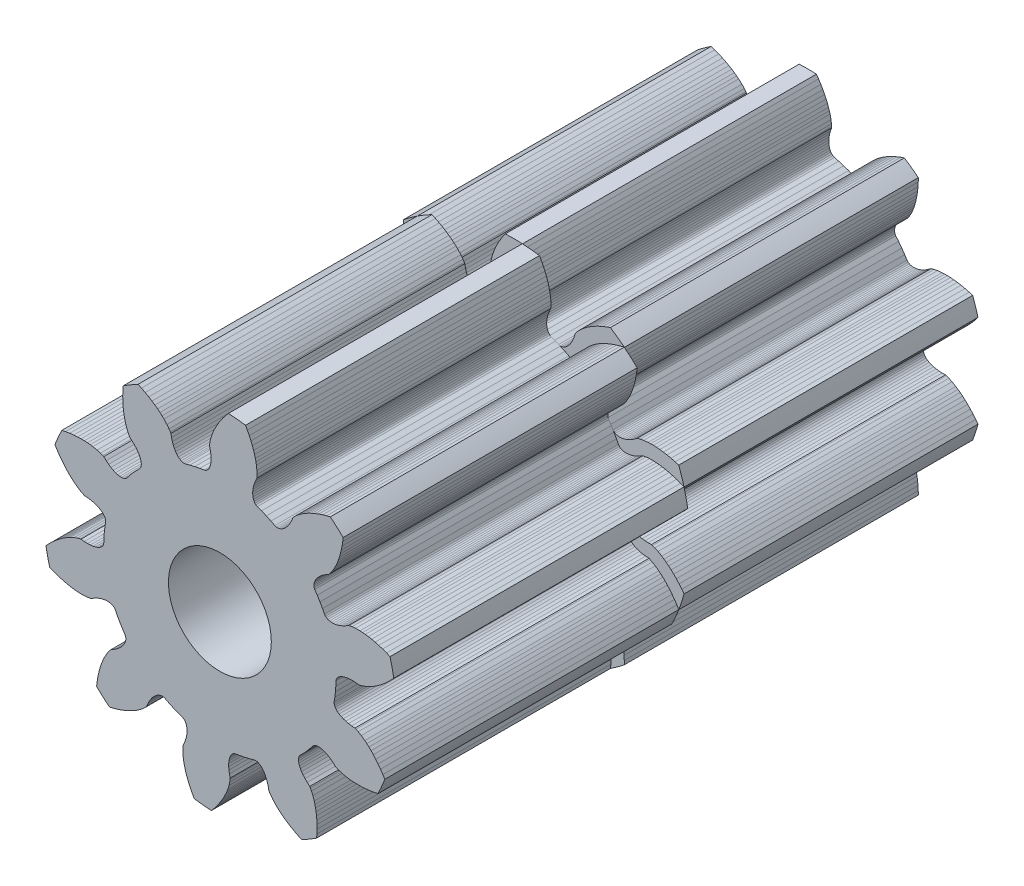
SolidWorks part; units mm, degrees
ref_plane "Front Plane" through (0, 0, 0) normal (0, 0, 1) x (1, 0, 0)
ref_plane "Top Plane" through (0, 0, 0) normal (0, 1, 0) x (1, 0, 0)
ref_plane "Right Plane" through (0, 0, 0) normal (1, 0, 0) x (0, 0, -1)
sketch "Sketch1" plane through (0, 0, 0) normal (0, 0, 1) x (1, 0, 0)
  line L0 (11.2428, -4.5485) -> (11.2517, -4.4039)
  line L1 (11.2517, -4.4039) -> (11.266, -4.2669)
  line L2 (11.266, -4.2669) -> (11.2847, -4.1393)
  line L3 (11.2847, -4.1393) -> (11.3071, -4.0209)
  line L4 (11.3071, -4.0209) -> (11.3325, -3.912)
  line L5 (11.3325, -3.912) -> (11.3608, -3.8103)
  line L6 (11.3608, -3.8103) -> (11.3897, -3.7211)
  line L7 (11.3897, -3.7211) -> (11.4208, -3.6371)
  line L8 (11.4208, -3.6371) -> (11.4807, -3.5016)
  line L9 (11.4807, -3.5016) -> (11.5377, -3.3971)
  line L10 (11.5377, -3.3971) -> (11.5845, -3.3262)
  line L11 (11.5845, -3.3262) -> (11.6076, -3.2964)
  line L12 (11.6076, -3.2964) -> (11.7007, -3.2317)
  line L13 (11.7007, -3.2317) -> (11.7827, -3.1653)
  line L14 (11.7827, -3.1653) -> (11.8533, -3.098)
  line L15 (11.8533, -3.098) -> (11.9128, -3.0308)
  line L16 (11.9128, -3.0308) -> (11.9612, -2.9643)
  line L17 (11.9612, -2.9643) -> (11.9989, -2.8995)
  line L18 (11.9989, -2.8995) -> (12.0259, -2.837)
  line L19 (12.0259, -2.837) -> (12.0426, -2.7776)
  line L20 (12.0426, -2.7776) -> (12.0493, -2.7222)
  line L21 (12.0493, -2.7222) -> (12.0463, -2.6714)
  line L22 (12.0463, -2.6714) -> (12.0342, -2.6259)
  line L23 (12.0342, -2.6259) -> (12.0067, -2.5776)
  line L24 (12.0067, -2.5776) -> (11.9109, -2.4617)
  line L25 (11.9109, -2.4617) -> (11.8044, -2.3217)
  line L26 (11.8044, -2.3217) -> (11.7041, -2.1772)
  line L27 (11.7041, -2.1772) -> (11.6236, -2.0503)
  line L28 (11.6236, -2.0503) -> (11.5861, -2.0092)
  line L29 (11.5861, -2.0092) -> (11.5466, -1.9836)
  line L30 (11.5466, -1.9836) -> (11.4992, -1.9651)
  line L31 (11.4992, -1.9651) -> (11.4444, -1.9543)
  line L32 (11.4444, -1.9543) -> (11.3828, -1.9518)
  line L33 (11.3828, -1.9518) -> (11.315, -1.9582)
  line L34 (11.315, -1.9582) -> (11.2417, -1.974)
  line L35 (11.2417, -1.974) -> (11.1635, -1.9995)
  line L36 (11.1635, -1.9995) -> (11.0812, -2.0353)
  line L37 (11.0812, -2.0353) -> (10.9954, -2.0817)
  line L38 (10.9954, -2.0817) -> (10.907, -2.1391)
  line L39 (10.907, -2.1391) -> (10.8166, -2.2077)
  line L40 (10.8166, -2.2077) -> (10.7811, -2.2204)
  line L41 (10.7811, -2.2204) -> (10.6992, -2.243)
  line L42 (10.6992, -2.243) -> (10.5823, -2.2649)
  line L43 (10.5823, -2.2649) -> (10.4348, -2.2801)
  line L44 (10.4348, -2.2801) -> (10.3453, -2.2837)
  line L45 (10.3453, -2.2837) -> (10.2516, -2.2836)
  line L46 (10.2516, -2.2836) -> (10.1461, -2.2791)
  line L47 (10.1461, -2.2791) -> (10.0348, -2.2696)
  line L48 (10.0348, -2.2696) -> (9.9151, -2.2543)
  line L49 (9.9151, -2.2543) -> (9.7881, -2.2327)
  line L50 (9.7881, -2.2327) -> (9.6533, -2.2039)
  line L51 (9.6533, -2.2039) -> (9.5131, -2.1677)
  line L52 (9.5131, -2.1677) -> (9.3912, -2.1311)
  line L53 (9.2098, -1.5726) -> (9.2868, -1.4714)
  line L54 (9.2868, -1.4714) -> (9.379, -1.3597)
  line L55 (9.379, -1.3597) -> (9.4711, -1.2572)
  line L56 (9.4711, -1.2572) -> (9.5612, -1.165)
  line L57 (9.5612, -1.165) -> (9.649, -1.0823)
  line L58 (9.649, -1.0823) -> (9.7335, -1.0092)
  line L59 (9.7335, -1.0092) -> (9.8162, -0.9435)
  line L60 (9.8162, -0.9435) -> (9.8919, -0.8883)
  line L61 (9.8919, -0.8883) -> (9.9665, -0.8387)
  line L62 (9.9665, -0.8387) -> (10.0947, -0.7642)
  line L63 (10.0947, -0.7642) -> (10.2021, -0.7133)
  line L64 (10.2021, -0.7133) -> (10.2817, -0.6834)
  line L65 (10.2817, -0.6834) -> (10.3179, -0.6728)
  line L66 (10.3179, -0.6728) -> (10.4313, -0.6752)
  line L67 (10.4313, -0.6752) -> (10.5366, -0.6696)
  line L68 (10.5366, -0.6696) -> (10.6333, -0.6568)
  line L69 (10.6333, -0.6568) -> (10.7209, -0.6373)
  line L70 (10.7209, -0.6373) -> (10.7992, -0.612)
  line L71 (10.7992, -0.612) -> (10.8678, -0.5817)
  line L72 (10.8678, -0.5817) -> (10.9263, -0.547)
  line L73 (10.9263, -0.547) -> (10.9747, -0.5088)
  line L74 (10.9747, -0.5088) -> (11.0127, -0.4679)
  line L75 (11.0127, -0.4679) -> (11.0402, -0.4251)
  line L76 (11.0402, -0.4251) -> (11.0571, -0.3811)
  line L77 (11.0571, -0.3811) -> (11.0633, -0.3259)
  line L78 (11.0633, -0.3259) -> (11.0539, -0.1759)
  line L79 (11.0539, -0.1759) -> (11.05, 0)
  line L80 (11.05, 0) -> (11.0539, 0.1759)
  line L81 (11.0539, 0.1759) -> (11.0633, 0.3259)
  line L82 (11.0633, 0.3259) -> (11.0571, 0.3812)
  line L83 (11.0571, 0.3812) -> (11.0402, 0.4251)
  line L84 (11.0402, 0.4251) -> (11.0127, 0.468)
  line L85 (11.0127, 0.468) -> (10.9747, 0.5089)
  line L86 (10.9747, 0.5089) -> (10.9263, 0.5471)
  line L87 (10.9263, 0.5471) -> (10.8678, 0.5817)
  line L88 (10.8678, 0.5817) -> (10.7992, 0.6121)
  line L89 (10.7992, 0.6121) -> (10.7209, 0.6374)
  line L90 (10.7209, 0.6374) -> (10.6333, 0.6568)
  line L91 (10.6333, 0.6568) -> (10.5366, 0.6697)
  line L92 (10.5366, 0.6697) -> (10.4313, 0.6753)
  line L93 (10.4313, 0.6753) -> (10.3179, 0.6729)
  line L94 (10.3179, 0.6729) -> (10.2817, 0.6834)
  line L95 (10.2817, 0.6834) -> (10.2021, 0.7133)
  line L96 (10.2021, 0.7133) -> (10.0947, 0.7643)
  line L97 (10.0947, 0.7643) -> (9.9665, 0.8387)
  line L98 (9.9665, 0.8387) -> (9.8919, 0.8884)
  line L99 (9.8919, 0.8884) -> (9.8162, 0.9436)
  line L100 (9.8162, 0.9436) -> (9.7335, 1.0093)
  line L101 (9.7335, 1.0093) -> (9.649, 1.0824)
  line L102 (9.649, 1.0824) -> (9.5612, 1.165)
  line L103 (9.5612, 1.165) -> (9.4711, 1.2572)
  line L104 (9.4711, 1.2572) -> (9.379, 1.3597)
  line L105 (9.379, 1.3597) -> (9.2868, 1.4714)
  line L106 (9.2868, 1.4714) -> (9.2098, 1.5727)
  line L107 (9.3912, 2.1311) -> (9.5131, 2.1677)
  line L108 (9.5131, 2.1677) -> (9.6533, 2.2039)
  line L109 (9.6533, 2.2039) -> (9.788, 2.2327)
  line L110 (9.788, 2.2327) -> (9.9151, 2.2544)
  line L111 (9.9151, 2.2544) -> (10.0347, 2.2696)
  line L112 (10.0347, 2.2696) -> (10.1461, 2.2791)
  line L113 (10.1461, 2.2791) -> (10.2516, 2.2836)
  line L114 (10.2516, 2.2836) -> (10.3453, 2.2837)
  line L115 (10.3453, 2.2837) -> (10.4348, 2.2801)
  line L116 (10.4348, 2.2801) -> (10.5823, 2.265)
  line L117 (10.5823, 2.265) -> (10.6992, 2.2431)
  line L118 (10.6992, 2.2431) -> (10.7811, 2.2205)
  line L119 (10.7811, 2.2205) -> (10.8166, 2.2078)
  line L120 (10.8166, 2.2078) -> (10.9069, 2.1391)
  line L121 (10.9069, 2.1391) -> (10.9954, 2.0818)
  line L122 (10.9954, 2.0818) -> (11.0812, 2.0353)
  line L123 (11.0812, 2.0353) -> (11.1635, 1.9995)
  line L124 (11.1635, 1.9995) -> (11.2417, 1.974)
  line L125 (11.2417, 1.974) -> (11.315, 1.9583)
  line L126 (11.315, 1.9583) -> (11.3828, 1.9519)
  line L127 (11.3828, 1.9519) -> (11.4444, 1.9543)
  line L128 (11.4444, 1.9543) -> (11.4991, 1.9651)
  line L129 (11.4991, 1.9651) -> (11.5465, 1.9836)
  line L130 (11.5465, 1.9836) -> (11.586, 2.0092)
  line L131 (11.586, 2.0092) -> (11.6235, 2.0503)
  line L132 (11.6235, 2.0503) -> (11.7041, 2.1772)
  line L133 (11.7041, 2.1772) -> (11.8043, 2.3218)
  line L134 (11.8043, 2.3218) -> (11.9109, 2.4618)
  line L135 (11.9109, 2.4618) -> (12.0067, 2.5776)
  line L136 (12.0067, 2.5776) -> (12.0341, 2.626)
  line L137 (12.0341, 2.626) -> (12.0463, 2.6715)
  line L138 (12.0463, 2.6715) -> (12.0492, 2.7223)
  line L139 (12.0492, 2.7223) -> (12.0426, 2.7777)
  line L140 (12.0426, 2.7777) -> (12.0259, 2.837)
  line L141 (12.0259, 2.837) -> (11.9988, 2.8995)
  line L142 (11.9988, 2.8995) -> (11.9612, 2.9643)
  line L143 (11.9612, 2.9643) -> (11.9128, 3.0308)
  line L144 (11.9128, 3.0308) -> (11.8533, 3.0981)
  line L145 (11.8533, 3.0981) -> (11.7826, 3.1653)
  line L146 (11.7826, 3.1653) -> (11.7007, 3.2317)
  line L147 (11.7007, 3.2317) -> (11.6075, 3.2964)
  line L148 (11.6075, 3.2964) -> (11.5845, 3.3262)
  line L149 (11.5845, 3.3262) -> (11.5377, 3.3972)
  line L150 (11.5377, 3.3972) -> (11.4807, 3.5016)
  line L151 (11.4807, 3.5016) -> (11.4208, 3.6372)
  line L152 (11.4208, 3.6372) -> (11.3896, 3.7212)
  line L153 (11.3896, 3.7212) -> (11.3608, 3.8103)
  line L154 (11.3608, 3.8103) -> (11.3325, 3.9121)
  line L155 (11.3325, 3.9121) -> (11.3071, 4.0209)
  line L156 (11.3071, 4.0209) -> (11.2846, 4.1394)
  line L157 (11.2846, 4.1394) -> (11.2659, 4.2669)
  line L158 (11.2659, 4.2669) -> (11.2517, 4.404)
  line L159 (11.2517, 4.404) -> (11.2428, 4.5485)
  line L160 (11.2428, 4.5485) -> (11.2399, 4.6757)
  line L161 (11.715, 5.0209) -> (11.8351, 4.9789)
  line L162 (11.8351, 4.9789) -> (11.9698, 4.9257)
  line L163 (11.9698, 4.9257) -> (12.0958, 4.8698)
  line L164 (12.0958, 4.8698) -> (12.2113, 4.8127)
  line L165 (12.2113, 4.8127) -> (12.3171, 4.7547)
  line L166 (12.3171, 4.7547) -> (12.4127, 4.6969)
  line L167 (12.4127, 4.6969) -> (12.5007, 4.6385)
  line L168 (12.5007, 4.6385) -> (12.5766, 4.5836)
  line L169 (12.5766, 4.5836) -> (12.6469, 4.528)
  line L170 (12.6469, 4.528) -> (12.7573, 4.4291)
  line L171 (12.7573, 4.4291) -> (12.839, 4.3427)
  line L172 (12.839, 4.3427) -> (12.892, 4.2762)
  line L173 (12.892, 4.2762) -> (12.9132, 4.2451)
  line L174 (12.9132, 4.2451) -> (12.946, 4.1364)
  line L175 (12.946, 4.1364) -> (12.9838, 4.038)
  line L176 (12.9838, 4.038) -> (13.0259, 3.9501)
  line L177 (13.0259, 3.9501) -> (13.0715, 3.8727)
  line L178 (13.0715, 3.8727) -> (13.1197, 3.8061)
  line L179 (13.1197, 3.8061) -> (13.1698, 3.7503)
  line L180 (13.1698, 3.7503) -> (13.2209, 3.7053)
  line L181 (13.2209, 3.7053) -> (13.2721, 3.671)
  line L182 (13.2721, 3.671) -> (13.3228, 3.6476)
  line L183 (13.3228, 3.6476) -> (13.372, 3.6347)
  line L184 (13.372, 3.6347) -> (13.419, 3.6322)
  line L185 (13.419, 3.6322) -> (13.4735, 3.6434)
  line L186 (13.4735, 3.6434) -> (13.6133, 3.6987)
  line L187 (13.6133, 3.6987) -> (13.7794, 3.7567)
  line L188 (13.7794, 3.7567) -> (13.9478, 3.8074)
  line L189 (13.9478, 3.8074) -> (14.0934, 3.8448)
  line L190 (14.0934, 3.8448) -> (14.1441, 3.8678)
  line L191 (14.1441, 3.8678) -> (14.1806, 3.8974)
  line L192 (14.1806, 3.8974) -> (14.2129, 3.9368)
  line L193 (14.2129, 3.9368) -> (14.2401, 3.9855)
  line L194 (14.2401, 3.9855) -> (14.2614, 4.0434)
  line L195 (14.2614, 4.0434) -> (14.2763, 4.1098)
  line L196 (14.2763, 4.1098) -> (14.284, 4.1844)
  line L197 (14.284, 4.1844) -> (14.2838, 4.2666)
  line L198 (14.2838, 4.2666) -> (14.2752, 4.356)
  line L199 (14.2752, 4.356) -> (14.2576, 4.4519)
  line L200 (14.2576, 4.4519) -> (14.2304, 4.5538)
  line L201 (14.2304, 4.5538) -> (14.193, 4.6609)
  line L202 (14.193, 4.6609) -> (14.1919, 4.6986)
  line L203 (14.1919, 4.6986) -> (14.1957, 4.7835)
  line L204 (14.1957, 4.7835) -> (14.211, 4.9014)
  line L205 (14.211, 4.9014) -> (14.2422, 5.0463)
  line L206 (14.2422, 5.0463) -> (14.2664, 5.1326)
  line L207 (14.2664, 5.1326) -> (14.2955, 5.2217)
  line L208 (14.2955, 5.2217) -> (14.3324, 5.3207)
  line L209 (14.3324, 5.3207) -> (14.3758, 5.4236)
  line L210 (14.3758, 5.4236) -> (14.4273, 5.5327)
  line L211 (14.4273, 5.5327) -> (14.4871, 5.6468)
  line L212 (14.4871, 5.6468) -> (14.5562, 5.7661)
  line L213 (14.5562, 5.7661) -> (14.6339, 5.8883)
  line L214 (14.6339, 5.8883) -> (14.7064, 5.9928)
  line L215 (15.2936, 5.9928) -> (15.3661, 5.8883)
  line L216 (15.3661, 5.8883) -> (15.4438, 5.7661)
  line L217 (15.4438, 5.7661) -> (15.5128, 5.6468)
  line L218 (15.5128, 5.6468) -> (15.5727, 5.5327)
  line L219 (15.5727, 5.5327) -> (15.6242, 5.4236)
  line L220 (15.6242, 5.4236) -> (15.6676, 5.3207)
  line L221 (15.6676, 5.3207) -> (15.7045, 5.2217)
  line L222 (15.7045, 5.2217) -> (15.7336, 5.1326)
  line L223 (15.7336, 5.1326) -> (15.7578, 5.0464)
  line L224 (15.7578, 5.0464) -> (15.7889, 4.9014)
  line L225 (15.7889, 4.9014) -> (15.8042, 4.7835)
  line L226 (15.8042, 4.7835) -> (15.8081, 4.6986)
  line L227 (15.8081, 4.6986) -> (15.8069, 4.6609)
  line L228 (15.8069, 4.6609) -> (15.7696, 4.5538)
  line L229 (15.7696, 4.5538) -> (15.7424, 4.4519)
  line L230 (15.7424, 4.4519) -> (15.7247, 4.356)
  line L231 (15.7247, 4.356) -> (15.7161, 4.2666)
  line L232 (15.7161, 4.2666) -> (15.716, 4.1844)
  line L233 (15.716, 4.1844) -> (15.7237, 4.1098)
  line L234 (15.7237, 4.1098) -> (15.7385, 4.0434)
  line L235 (15.7385, 4.0434) -> (15.7599, 3.9855)
  line L236 (15.7599, 3.9855) -> (15.7871, 3.9368)
  line L237 (15.7871, 3.9368) -> (15.8193, 3.8974)
  line L238 (15.8193, 3.8974) -> (15.8559, 3.8678)
  line L239 (15.8559, 3.8678) -> (15.9065, 3.8448)
  line L240 (15.9065, 3.8448) -> (16.0521, 3.8074)
  line L241 (16.0521, 3.8074) -> (16.2206, 3.7567)
  line L242 (16.2206, 3.7567) -> (16.3867, 3.6987)
  line L243 (16.3867, 3.6987) -> (16.5264, 3.6434)
  line L244 (16.5264, 3.6434) -> (16.5809, 3.6322)
  line L245 (16.5809, 3.6322) -> (16.6279, 3.6347)
  line L246 (16.6279, 3.6347) -> (16.6772, 3.6476)
  line L247 (16.6772, 3.6476) -> (16.7278, 3.6711)
  line L248 (16.7278, 3.6711) -> (16.7791, 3.7053)
  line L249 (16.7791, 3.7053) -> (16.8301, 3.7503)
  line L250 (16.8301, 3.7503) -> (16.8802, 3.8061)
  line L251 (16.8802, 3.8061) -> (16.9284, 3.8727)
  line L252 (16.9284, 3.8727) -> (16.974, 3.9501)
  line L253 (16.974, 3.9501) -> (17.0161, 4.038)
  line L254 (17.0161, 4.038) -> (17.054, 4.1365)
  line L255 (17.054, 4.1365) -> (17.0867, 4.2451)
  line L256 (17.0867, 4.2451) -> (17.108, 4.2762)
  line L257 (17.108, 4.2762) -> (17.161, 4.3427)
  line L258 (17.161, 4.3427) -> (17.2427, 4.4291)
  line L259 (17.2427, 4.4291) -> (17.3531, 4.528)
  line L260 (17.3531, 4.528) -> (17.4233, 4.5836)
  line L261 (17.4233, 4.5836) -> (17.4992, 4.6385)
  line L262 (17.4992, 4.6385) -> (17.5873, 4.6969)
  line L263 (17.5873, 4.6969) -> (17.6829, 4.7547)
  line L264 (17.6829, 4.7547) -> (17.7886, 4.8127)
  line L265 (17.7886, 4.8127) -> (17.9042, 4.8699)
  line L266 (17.9042, 4.8699) -> (18.0301, 4.9258)
  line L267 (18.0301, 4.9258) -> (18.1648, 4.9789)
  line L268 (18.1648, 4.9789) -> (18.2849, 5.0209)
  line L269 (18.76, 4.6758) -> (18.7572, 4.5486)
  line L270 (18.7572, 4.5486) -> (18.7483, 4.404)
  line L271 (18.7483, 4.404) -> (18.734, 4.2669)
  line L272 (18.734, 4.2669) -> (18.7153, 4.1394)
  line L273 (18.7153, 4.1394) -> (18.6928, 4.0209)
  line L274 (18.6928, 4.0209) -> (18.6675, 3.9121)
  line L275 (18.6675, 3.9121) -> (18.6392, 3.8103)
  line L276 (18.6392, 3.8103) -> (18.6103, 3.7212)
  line L277 (18.6103, 3.7212) -> (18.5792, 3.6372)
  line L278 (18.5792, 3.6372) -> (18.5192, 3.5016)
  line L279 (18.5192, 3.5016) -> (18.4623, 3.3972)
  line L280 (18.4623, 3.3972) -> (18.4155, 3.3263)
  line L281 (18.4155, 3.3263) -> (18.3924, 3.2965)
  line L282 (18.3924, 3.2965) -> (18.2992, 3.2317)
  line L283 (18.2992, 3.2317) -> (18.2173, 3.1653)
  line L284 (18.2173, 3.1653) -> (18.1467, 3.0981)
  line L285 (18.1467, 3.0981) -> (18.0872, 3.0308)
  line L286 (18.0872, 3.0308) -> (18.0387, 2.9644)
  line L287 (18.0387, 2.9644) -> (18.0011, 2.8995)
  line L288 (18.0011, 2.8995) -> (17.9741, 2.837)
  line L289 (17.9741, 2.837) -> (17.9574, 2.7777)
  line L290 (17.9574, 2.7777) -> (17.9507, 2.7223)
  line L291 (17.9507, 2.7223) -> (17.9537, 2.6715)
  line L292 (17.9537, 2.6715) -> (17.9658, 2.626)
  line L293 (17.9658, 2.626) -> (17.9933, 2.5777)
  line L294 (17.9933, 2.5777) -> (18.0891, 2.4618)
  line L295 (18.0891, 2.4618) -> (18.1956, 2.3218)
  line L296 (18.1956, 2.3218) -> (18.2959, 2.1772)
  line L297 (18.2959, 2.1772) -> (18.3764, 2.0503)
  line L298 (18.3764, 2.0503) -> (18.4139, 2.0093)
  line L299 (18.4139, 2.0093) -> (18.4534, 1.9836)
  line L300 (18.4534, 1.9836) -> (18.5008, 1.9651)
  line L301 (18.5008, 1.9651) -> (18.5556, 1.9544)
  line L302 (18.5556, 1.9544) -> (18.6172, 1.9519)
  line L303 (18.6172, 1.9519) -> (18.6849, 1.9583)
  line L304 (18.6849, 1.9583) -> (18.7583, 1.974)
  line L305 (18.7583, 1.974) -> (18.8364, 1.9996)
  line L306 (18.8364, 1.9996) -> (18.9188, 2.0354)
  line L307 (18.9188, 2.0354) -> (19.0046, 2.0818)
  line L308 (19.0046, 2.0818) -> (19.093, 2.1392)
  line L309 (19.093, 2.1392) -> (19.1834, 2.2078)
  line L310 (19.1834, 2.2078) -> (19.2188, 2.2205)
  line L311 (19.2188, 2.2205) -> (19.3008, 2.2431)
  line L312 (19.3008, 2.2431) -> (19.4177, 2.265)
  line L313 (19.4177, 2.265) -> (19.5651, 2.2801)
  line L314 (19.5651, 2.2801) -> (19.6547, 2.2838)
  line L315 (19.6547, 2.2838) -> (19.7484, 2.2837)
  line L316 (19.7484, 2.2837) -> (19.8539, 2.2791)
  line L317 (19.8539, 2.2791) -> (19.9652, 2.2696)
  line L318 (19.9652, 2.2696) -> (20.0848, 2.2544)
  line L319 (20.0848, 2.2544) -> (20.2119, 2.2328)
  line L320 (20.2119, 2.2328) -> (20.3467, 2.204)
  line L321 (20.3467, 2.204) -> (20.4869, 2.1678)
  line L322 (20.4869, 2.1678) -> (20.6088, 2.1312)
  line L323 (20.7902, 1.5727) -> (20.7132, 1.4714)
  line L324 (20.7132, 1.4714) -> (20.621, 1.3598)
  line L325 (20.621, 1.3598) -> (20.5289, 1.2572)
  line L326 (20.5289, 1.2572) -> (20.4388, 1.165)
  line L327 (20.4388, 1.165) -> (20.351, 1.0824)
  line L328 (20.351, 1.0824) -> (20.2665, 1.0093)
  line L329 (20.2665, 1.0093) -> (20.1838, 0.9436)
  line L330 (20.1838, 0.9436) -> (20.108, 0.8884)
  line L331 (20.108, 0.8884) -> (20.0335, 0.8388)
  line L332 (20.0335, 0.8388) -> (19.9053, 0.7643)
  line L333 (19.9053, 0.7643) -> (19.7979, 0.7133)
  line L334 (19.7979, 0.7133) -> (19.7183, 0.6834)
  line L335 (19.7183, 0.6834) -> (19.6821, 0.6729)
  line L336 (19.6821, 0.6729) -> (19.5687, 0.6753)
  line L337 (19.5687, 0.6753) -> (19.4634, 0.6697)
  line L338 (19.4634, 0.6697) -> (19.3667, 0.6568)
  line L339 (19.3667, 0.6568) -> (19.279, 0.6374)
  line L340 (19.279, 0.6374) -> (19.2008, 0.6121)
  line L341 (19.2008, 0.6121) -> (19.1322, 0.5818)
  line L342 (19.1322, 0.5818) -> (19.0736, 0.5471)
  line L343 (19.0736, 0.5471) -> (19.0253, 0.5089)
  line L344 (19.0253, 0.5089) -> (18.9873, 0.468)
  line L345 (18.9873, 0.468) -> (18.9598, 0.4252)
  line L346 (18.9598, 0.4252) -> (18.9429, 0.3812)
  line L347 (18.9429, 0.3812) -> (18.9367, 0.3259)
  line L348 (18.9367, 0.3259) -> (18.9461, 0.1759)
  line L349 (18.9461, 0.1759) -> (18.95, 0)
  line L350 (18.95, 0) -> (18.9461, -0.1758)
  line L351 (18.9461, -0.1758) -> (18.9367, -0.3259)
  line L352 (18.9367, -0.3259) -> (18.9429, -0.3811)
  line L353 (18.9429, -0.3811) -> (18.9598, -0.4251)
  line L354 (18.9598, -0.4251) -> (18.9873, -0.4679)
  line L355 (18.9873, -0.4679) -> (19.0253, -0.5088)
  line L356 (19.0253, -0.5088) -> (19.0736, -0.547)
  line L357 (19.0736, -0.547) -> (19.1322, -0.5817)
  line L358 (19.1322, -0.5817) -> (19.2008, -0.612)
  line L359 (19.2008, -0.612) -> (19.279, -0.6373)
  line L360 (19.279, -0.6373) -> (19.3667, -0.6567)
  line L361 (19.3667, -0.6567) -> (19.4634, -0.6696)
  line L362 (19.4634, -0.6696) -> (19.5687, -0.6752)
  line L363 (19.5687, -0.6752) -> (19.6821, -0.6728)
  line L364 (19.6821, -0.6728) -> (19.7183, -0.6834)
  line L365 (19.7183, -0.6834) -> (19.7979, -0.7132)
  line L366 (19.7979, -0.7132) -> (19.9053, -0.7642)
  line L367 (19.9053, -0.7642) -> (20.0335, -0.8387)
  line L368 (20.0335, -0.8387) -> (20.108, -0.8883)
  line L369 (20.108, -0.8883) -> (20.1838, -0.9435)
  line L370 (20.1838, -0.9435) -> (20.2665, -1.0092)
  line L371 (20.2665, -1.0092) -> (20.351, -1.0823)
  line L372 (20.351, -1.0823) -> (20.4388, -1.1649)
  line L373 (20.4388, -1.1649) -> (20.5289, -1.2571)
  line L374 (20.5289, -1.2571) -> (20.621, -1.3597)
  line L375 (20.621, -1.3597) -> (20.7132, -1.4714)
  line L376 (20.7132, -1.4714) -> (20.7902, -1.5726)
  line L377 (20.6088, -2.131) -> (20.4869, -2.1677)
  line L378 (20.4869, -2.1677) -> (20.3467, -2.2039)
  line L379 (20.3467, -2.2039) -> (20.2119, -2.2327)
  line L380 (20.2119, -2.2327) -> (20.0849, -2.2543)
  line L381 (20.0849, -2.2543) -> (19.9652, -2.2695)
  line L382 (19.9652, -2.2695) -> (19.8539, -2.279)
  line L383 (19.8539, -2.279) -> (19.7484, -2.2836)
  line L384 (19.7484, -2.2836) -> (19.6547, -2.2837)
  line L385 (19.6547, -2.2837) -> (19.5652, -2.28)
  line L386 (19.5652, -2.28) -> (19.4177, -2.2649)
  line L387 (19.4177, -2.2649) -> (19.3008, -2.243)
  line L388 (19.3008, -2.243) -> (19.2189, -2.2204)
  line L389 (19.2189, -2.2204) -> (19.1834, -2.2077)
  line L390 (19.1834, -2.2077) -> (19.093, -2.1391)
  line L391 (19.093, -2.1391) -> (19.0046, -2.0817)
  line L392 (19.0046, -2.0817) -> (18.9188, -2.0353)
  line L393 (18.9188, -2.0353) -> (18.8365, -1.9995)
  line L394 (18.8365, -1.9995) -> (18.7583, -1.9739)
  line L395 (18.7583, -1.9739) -> (18.685, -1.9582)
  line L396 (18.685, -1.9582) -> (18.6172, -1.9518)
  line L397 (18.6172, -1.9518) -> (18.5556, -1.9543)
  line L398 (18.5556, -1.9543) -> (18.5008, -1.965)
  line L399 (18.5008, -1.965) -> (18.4534, -1.9835)
  line L400 (18.4534, -1.9835) -> (18.4139, -2.0092)
  line L401 (18.4139, -2.0092) -> (18.3764, -2.0502)
  line L402 (18.3764, -2.0502) -> (18.2959, -2.1771)
  line L403 (18.2959, -2.1771) -> (18.1956, -2.3217)
  line L404 (18.1956, -2.3217) -> (18.0891, -2.4617)
  line L405 (18.0891, -2.4617) -> (17.9933, -2.5776)
  line L406 (17.9933, -2.5776) -> (17.9658, -2.6259)
  line L407 (17.9658, -2.6259) -> (17.9537, -2.6714)
  line L408 (17.9537, -2.6714) -> (17.9507, -2.7222)
  line L409 (17.9507, -2.7222) -> (17.9574, -2.7776)
  line L410 (17.9574, -2.7776) -> (17.9741, -2.8369)
  line L411 (17.9741, -2.8369) -> (18.0011, -2.8994)
  line L412 (18.0011, -2.8994) -> (18.0387, -2.9643)
  line L413 (18.0387, -2.9643) -> (18.0872, -3.0307)
  line L414 (18.0872, -3.0307) -> (18.1467, -3.098)
  line L415 (18.1467, -3.098) -> (18.2173, -3.1652)
  line L416 (18.2173, -3.1652) -> (18.2992, -3.2316)
  line L417 (18.2992, -3.2316) -> (18.3924, -3.2964)
  line L418 (18.3924, -3.2964) -> (18.4155, -3.3262)
  line L419 (18.4155, -3.3262) -> (18.4623, -3.3971)
  line L420 (18.4623, -3.3971) -> (18.5193, -3.5015)
  line L421 (18.5193, -3.5015) -> (18.5792, -3.6371)
  line L422 (18.5792, -3.6371) -> (18.6103, -3.7211)
  line L423 (18.6103, -3.7211) -> (18.6392, -3.8102)
  line L424 (18.6392, -3.8102) -> (18.6675, -3.912)
  line L425 (18.6675, -3.912) -> (18.6929, -4.0208)
  line L426 (18.6929, -4.0208) -> (18.7153, -4.1393)
  line L427 (18.7153, -4.1393) -> (18.734, -4.2668)
  line L428 (18.734, -4.2668) -> (18.7483, -4.4039)
  line L429 (18.7483, -4.4039) -> (18.7572, -4.5484)
  line L430 (18.7572, -4.5484) -> (18.76, -4.6757)
  line L431 (18.285, -5.0208) -> (18.1648, -4.9788)
  line L432 (18.1648, -4.9788) -> (18.0301, -4.9257)
  line L433 (18.0301, -4.9257) -> (17.9042, -4.8698)
  line L434 (17.9042, -4.8698) -> (17.7886, -4.8126)
  line L435 (17.7886, -4.8126) -> (17.6829, -4.7546)
  line L436 (17.6829, -4.7546) -> (17.5873, -4.6968)
  line L437 (17.5873, -4.6968) -> (17.4992, -4.6385)
  line L438 (17.4992, -4.6385) -> (17.4234, -4.5835)
  line L439 (17.4234, -4.5835) -> (17.3531, -4.5279)
  line L440 (17.3531, -4.5279) -> (17.2427, -4.429)
  line L441 (17.2427, -4.429) -> (17.161, -4.3426)
  line L442 (17.161, -4.3426) -> (17.108, -4.2761)
  line L443 (17.108, -4.2761) -> (17.0868, -4.245)
  line L444 (17.0868, -4.245) -> (17.054, -4.1364)
  line L445 (17.054, -4.1364) -> (17.0161, -4.038)
  line L446 (17.0161, -4.038) -> (16.974, -3.95)
  line L447 (16.974, -3.95) -> (16.9284, -3.8726)
  line L448 (16.9284, -3.8726) -> (16.8802, -3.806)
  line L449 (16.8802, -3.806) -> (16.8302, -3.7502)
  line L450 (16.8302, -3.7502) -> (16.7791, -3.7052)
  line L451 (16.7791, -3.7052) -> (16.7278, -3.671)
  line L452 (16.7278, -3.671) -> (16.6772, -3.6475)
  line L453 (16.6772, -3.6475) -> (16.6279, -3.6346)
  line L454 (16.6279, -3.6346) -> (16.5809, -3.6321)
  line L455 (16.5809, -3.6321) -> (16.5265, -3.6433)
  line L456 (16.5265, -3.6433) -> (16.3867, -3.6986)
  line L457 (16.3867, -3.6986) -> (16.2206, -3.7567)
  line L458 (16.2206, -3.7567) -> (16.0521, -3.8073)
  line L459 (16.0521, -3.8073) -> (15.9066, -3.8447)
  line L460 (15.9066, -3.8447) -> (15.8559, -3.8677)
  line L461 (15.8559, -3.8677) -> (15.8193, -3.8973)
  line L462 (15.8193, -3.8973) -> (15.7871, -3.9367)
  line L463 (15.7871, -3.9367) -> (15.7599, -3.9855)
  line L464 (15.7599, -3.9855) -> (15.7385, -4.0433)
  line L465 (15.7385, -4.0433) -> (15.7237, -4.1097)
  line L466 (15.7237, -4.1097) -> (15.716, -4.1843)
  line L467 (15.716, -4.1843) -> (15.7161, -4.2665)
  line L468 (15.7161, -4.2665) -> (15.7247, -4.3559)
  line L469 (15.7247, -4.3559) -> (15.7424, -4.4518)
  line L470 (15.7424, -4.4518) -> (15.7696, -4.5537)
  line L471 (15.7696, -4.5537) -> (15.8069, -4.6609)
  line L472 (15.8069, -4.6609) -> (15.8081, -4.6985)
  line L473 (15.8081, -4.6985) -> (15.8042, -4.7834)
  line L474 (15.8042, -4.7834) -> (15.789, -4.9014)
  line L475 (15.789, -4.9014) -> (15.7578, -5.0463)
  line L476 (15.7578, -5.0463) -> (15.7336, -5.1325)
  line L477 (15.7336, -5.1325) -> (15.7045, -5.2216)
  line L478 (15.7045, -5.2216) -> (15.6676, -5.3206)
  line L479 (15.6676, -5.3206) -> (15.6242, -5.4235)
  line L480 (15.6242, -5.4235) -> (15.5727, -5.5326)
  line L481 (15.5727, -5.5326) -> (15.5129, -5.6468)
  line L482 (15.5129, -5.6468) -> (15.4438, -5.766)
  line L483 (15.4438, -5.766) -> (15.3661, -5.8882)
  line L484 (15.3661, -5.8882) -> (15.2936, -5.9928)
  line L485 (14.7064, -5.9928) -> (14.6339, -5.8882)
  line L486 (14.6339, -5.8882) -> (14.5561, -5.766)
  line L487 (14.5561, -5.766) -> (14.4871, -5.6468)
  line L488 (14.4871, -5.6468) -> (14.4272, -5.5326)
  line L489 (14.4272, -5.5326) -> (14.3758, -5.4235)
  line L490 (14.3758, -5.4235) -> (14.3324, -5.3206)
  line L491 (14.3324, -5.3206) -> (14.2954, -5.2216)
  line L492 (14.2954, -5.2216) -> (14.2664, -5.1325)
  line L493 (14.2664, -5.1325) -> (14.2422, -5.0463)
  line L494 (14.2422, -5.0463) -> (14.211, -4.9014)
  line L495 (14.211, -4.9014) -> (14.1957, -4.7834)
  line L496 (14.1957, -4.7834) -> (14.1919, -4.6985)
  line L497 (14.1919, -4.6985) -> (14.193, -4.6608)
  line L498 (14.193, -4.6608) -> (14.2304, -4.5537)
  line L499 (14.2304, -4.5537) -> (14.2576, -4.4518)
  line L500 (14.2576, -4.4518) -> (14.2752, -4.3559)
  line L501 (14.2752, -4.3559) -> (14.2838, -4.2665)
  line L502 (14.2838, -4.2665) -> (14.284, -4.1843)
  line L503 (14.284, -4.1843) -> (14.2763, -4.1097)
  line L504 (14.2763, -4.1097) -> (14.2614, -4.0433)
  line L505 (14.2614, -4.0433) -> (14.24, -3.9855)
  line L506 (14.24, -3.9855) -> (14.2129, -3.9367)
  line L507 (14.2129, -3.9367) -> (14.1806, -3.8973)
  line L508 (14.1806, -3.8973) -> (14.144, -3.8677)
  line L509 (14.144, -3.8677) -> (14.0934, -3.8447)
  line L510 (14.0934, -3.8447) -> (13.9478, -3.8073)
  line L511 (13.9478, -3.8073) -> (13.7793, -3.7567)
  line L512 (13.7793, -3.7567) -> (13.6133, -3.6986)
  line L513 (13.6133, -3.6986) -> (13.4735, -3.6433)
  line L514 (13.4735, -3.6433) -> (13.419, -3.6321)
  line L515 (13.419, -3.6321) -> (13.372, -3.6346)
  line L516 (13.372, -3.6346) -> (13.3228, -3.6475)
  line L517 (13.3228, -3.6475) -> (13.2721, -3.671)
  line L518 (13.2721, -3.671) -> (13.2209, -3.7052)
  line L519 (13.2209, -3.7052) -> (13.1698, -3.7502)
  line L520 (13.1698, -3.7502) -> (13.1197, -3.806)
  line L521 (13.1197, -3.806) -> (13.0715, -3.8726)
  line L522 (13.0715, -3.8726) -> (13.0259, -3.95)
  line L523 (13.0259, -3.95) -> (12.9838, -4.038)
  line L524 (12.9838, -4.038) -> (12.946, -4.1364)
  line L525 (12.946, -4.1364) -> (12.9132, -4.245)
  line L526 (12.9132, -4.245) -> (12.892, -4.2761)
  line L527 (12.892, -4.2761) -> (12.839, -4.3426)
  line L528 (12.839, -4.3426) -> (12.7573, -4.429)
  line L529 (12.7573, -4.429) -> (12.6469, -4.5279)
  line L530 (12.6469, -4.5279) -> (12.5766, -4.5835)
  line L531 (12.5766, -4.5835) -> (12.5007, -4.6385)
  line L532 (12.5007, -4.6385) -> (12.4127, -4.6968)
  line L533 (12.4127, -4.6968) -> (12.317, -4.7546)
  line L534 (12.317, -4.7546) -> (12.2113, -4.8126)
  line L535 (12.2113, -4.8126) -> (12.0958, -4.8698)
  line L536 (12.0958, -4.8698) -> (11.9698, -4.9257)
  line L537 (11.9698, -4.9257) -> (11.8351, -4.9788)
  line L538 (11.8351, -4.9788) -> (11.715, -5.0208)
  line L539 (11.24, -4.6757) -> (11.2428, -4.5485)
  line L540 (11.2428, -4.5485) -> (11.2517, -4.4039)
  line L541 (11.2517, -4.4039) -> (11.266, -4.2669)
  line L542 (11.266, -4.2669) -> (11.2847, -4.1393)
  line L543 (11.2847, -4.1393) -> (11.3071, -4.0209)
  line L544 (11.3071, -4.0209) -> (11.3325, -3.912)
  line L545 (11.3325, -3.912) -> (11.3608, -3.8103)
  line L546 (11.3608, -3.8103) -> (11.3897, -3.7211)
  line L547 (11.3897, -3.7211) -> (11.4208, -3.6371)
  line L548 (11.4208, -3.6371) -> (11.4807, -3.5016)
  line L549 (11.4807, -3.5016) -> (11.5377, -3.3971)
  line L550 (11.5377, -3.3971) -> (11.5845, -3.3262)
  line L551 (11.5845, -3.3262) -> (11.6076, -3.2964)
  line L552 (11.6076, -3.2964) -> (11.7007, -3.2317)
  line L553 (11.7007, -3.2317) -> (11.7827, -3.1653)
  line L554 (11.7827, -3.1653) -> (11.8533, -3.098)
  line L555 (11.8533, -3.098) -> (11.9128, -3.0308)
  line L556 (11.9128, -3.0308) -> (11.9612, -2.9643)
  line L557 (11.9612, -2.9643) -> (11.9989, -2.8995)
  line L558 (11.9989, -2.8995) -> (12.0259, -2.837)
  line L559 (12.0259, -2.837) -> (12.0426, -2.7776)
  line L560 (12.0426, -2.7776) -> (12.0493, -2.7222)
  line L561 (12.0493, -2.7222) -> (12.0463, -2.6714)
  line L562 (12.0463, -2.6714) -> (12.0342, -2.6259)
  line L563 (12.0342, -2.6259) -> (12.0067, -2.5776)
  line L564 (12.0067, -2.5776) -> (11.9109, -2.4617)
  line L565 (11.9109, -2.4617) -> (11.8044, -2.3217)
  line L566 (11.8044, -2.3217) -> (11.7041, -2.1772)
  line L567 (11.7041, -2.1772) -> (11.6236, -2.0503)
  line L568 (11.6236, -2.0503) -> (11.5861, -2.0092)
  line L569 (11.5861, -2.0092) -> (11.5466, -1.9836)
  line L570 (11.5466, -1.9836) -> (11.4992, -1.9651)
  line L571 (11.4992, -1.9651) -> (11.4444, -1.9543)
  line L572 (11.4444, -1.9543) -> (11.3828, -1.9518)
  line L573 (11.3828, -1.9518) -> (11.315, -1.9582)
  line L574 (11.315, -1.9582) -> (11.2417, -1.974)
  line L575 (11.2417, -1.974) -> (11.1635, -1.9995)
  line L576 (11.1635, -1.9995) -> (11.0812, -2.0353)
  line L577 (11.0812, -2.0353) -> (10.9954, -2.0817)
  line L578 (10.9954, -2.0817) -> (10.907, -2.1391)
  line L579 (10.907, -2.1391) -> (10.8166, -2.2077)
  line L580 (10.8166, -2.2077) -> (10.7811, -2.2204)
  line L581 (10.7811, -2.2204) -> (10.6992, -2.243)
  line L582 (10.6992, -2.243) -> (10.5823, -2.2649)
  line L583 (10.5823, -2.2649) -> (10.4348, -2.2801)
  line L584 (10.4348, -2.2801) -> (10.3453, -2.2837)
  line L585 (10.3453, -2.2837) -> (10.2516, -2.2836)
  line L586 (10.2516, -2.2836) -> (10.1461, -2.2791)
  line L587 (10.1461, -2.2791) -> (10.0348, -2.2696)
  line L588 (10.0348, -2.2696) -> (9.9151, -2.2543)
  line L589 (9.9151, -2.2543) -> (9.7881, -2.2327)
  line L590 (9.7881, -2.2327) -> (9.6533, -2.2039)
  line L591 (9.6533, -2.2039) -> (9.5131, -2.1677)
  line L592 (9.5131, -2.1677) -> (9.3912, -2.1311)
  line L593 (9.2098, -1.5726) -> (9.2868, -1.4714)
  line L594 (9.2868, -1.4714) -> (9.379, -1.3597)
  line L595 (9.379, -1.3597) -> (9.4711, -1.2572)
  line L596 (9.4711, -1.2572) -> (9.5612, -1.165)
  line L597 (9.5612, -1.165) -> (9.649, -1.0823)
  line L598 (9.649, -1.0823) -> (9.7335, -1.0092)
  line L599 (9.7335, -1.0092) -> (9.8162, -0.9435)
  line L600 (9.8162, -0.9435) -> (9.8919, -0.8883)
  line L601 (9.8919, -0.8883) -> (9.9665, -0.8387)
  line L602 (9.9665, -0.8387) -> (10.0947, -0.7642)
  line L603 (10.0947, -0.7642) -> (10.2021, -0.7133)
  line L604 (10.2021, -0.7133) -> (10.2817, -0.6834)
  line L605 (10.2817, -0.6834) -> (10.3179, -0.6728)
  line L606 (10.3179, -0.6728) -> (10.4313, -0.6752)
  line L607 (10.4313, -0.6752) -> (10.5366, -0.6696)
  line L608 (10.5366, -0.6696) -> (10.6333, -0.6568)
  line L609 (10.6333, -0.6568) -> (10.7209, -0.6373)
  line L610 (10.7209, -0.6373) -> (10.7992, -0.612)
  line L611 (10.7992, -0.612) -> (10.8678, -0.5817)
  line L612 (10.8678, -0.5817) -> (10.9263, -0.547)
  line L613 (10.9263, -0.547) -> (10.9747, -0.5088)
  line L614 (10.9747, -0.5088) -> (11.0127, -0.4679)
  line L615 (11.0127, -0.4679) -> (11.0402, -0.4251)
  line L616 (11.0402, -0.4251) -> (11.0571, -0.3811)
  line L617 (11.0571, -0.3811) -> (11.0633, -0.3259)
  line L618 (11.0633, -0.3259) -> (11.0539, -0.1759)
  line L619 (11.0539, -0.1759) -> (11.05, 0)
  line L620 (11.05, 0) -> (11.0539, 0.1759)
  line L621 (11.0539, 0.1759) -> (11.0633, 0.3259)
  line L622 (11.0633, 0.3259) -> (11.0571, 0.3812)
  line L623 (11.0571, 0.3812) -> (11.0402, 0.4251)
  line L624 (11.0402, 0.4251) -> (11.0127, 0.468)
  line L625 (11.0127, 0.468) -> (10.9747, 0.5089)
  line L626 (10.9747, 0.5089) -> (10.9263, 0.5471)
  line L627 (10.9263, 0.5471) -> (10.8678, 0.5817)
  line L628 (10.8678, 0.5817) -> (10.7992, 0.6121)
  line L629 (10.7992, 0.6121) -> (10.7209, 0.6374)
  line L630 (10.7209, 0.6374) -> (10.6333, 0.6568)
  line L631 (10.6333, 0.6568) -> (10.5366, 0.6697)
  line L632 (10.5366, 0.6697) -> (10.4313, 0.6753)
  line L633 (10.4313, 0.6753) -> (10.3179, 0.6729)
  line L634 (10.3179, 0.6729) -> (10.2817, 0.6834)
  line L635 (10.2817, 0.6834) -> (10.2021, 0.7133)
  line L636 (10.2021, 0.7133) -> (10.0947, 0.7643)
  line L637 (10.0947, 0.7643) -> (9.9665, 0.8387)
  line L638 (9.9665, 0.8387) -> (9.8919, 0.8884)
  line L639 (9.8919, 0.8884) -> (9.8162, 0.9436)
  line L640 (9.8162, 0.9436) -> (9.7335, 1.0093)
  line L641 (9.7335, 1.0093) -> (9.649, 1.0824)
  line L642 (9.649, 1.0824) -> (9.5612, 1.165)
  line L643 (9.5612, 1.165) -> (9.4711, 1.2572)
  line L644 (9.4711, 1.2572) -> (9.379, 1.3597)
  line L645 (9.379, 1.3597) -> (9.2868, 1.4714)
  line L646 (9.2868, 1.4714) -> (9.2098, 1.5727)
  line L647 (9.3912, 2.1311) -> (9.5131, 2.1677)
  line L648 (9.5131, 2.1677) -> (9.6533, 2.2039)
  line L649 (9.6533, 2.2039) -> (9.788, 2.2327)
  line L650 (9.788, 2.2327) -> (9.9151, 2.2544)
  line L651 (9.9151, 2.2544) -> (10.0347, 2.2696)
  line L652 (10.0347, 2.2696) -> (10.1461, 2.2791)
  line L653 (10.1461, 2.2791) -> (10.2516, 2.2836)
  line L654 (10.2516, 2.2836) -> (10.3453, 2.2837)
  line L655 (10.3453, 2.2837) -> (10.4348, 2.2801)
  line L656 (10.4348, 2.2801) -> (10.5823, 2.265)
  line L657 (10.5823, 2.265) -> (10.6992, 2.2431)
  line L658 (10.6992, 2.2431) -> (10.7811, 2.2205)
  line L659 (10.7811, 2.2205) -> (10.8166, 2.2078)
  line L660 (10.8166, 2.2078) -> (10.9069, 2.1391)
  line L661 (10.9069, 2.1391) -> (10.9954, 2.0818)
  line L662 (10.9954, 2.0818) -> (11.0812, 2.0353)
  line L663 (11.0812, 2.0353) -> (11.1635, 1.9995)
  line L664 (11.1635, 1.9995) -> (11.2417, 1.974)
  line L665 (11.2417, 1.974) -> (11.315, 1.9583)
  line L666 (11.315, 1.9583) -> (11.3828, 1.9519)
  line L667 (11.3828, 1.9519) -> (11.4444, 1.9543)
  line L668 (11.4444, 1.9543) -> (11.4991, 1.9651)
  line L669 (11.4991, 1.9651) -> (11.5465, 1.9836)
  line L670 (11.5465, 1.9836) -> (11.586, 2.0092)
  line L671 (11.586, 2.0092) -> (11.6235, 2.0503)
  line L672 (11.6235, 2.0503) -> (11.7041, 2.1772)
  line L673 (11.7041, 2.1772) -> (11.8043, 2.3218)
  line L674 (11.8043, 2.3218) -> (11.9109, 2.4618)
  line L675 (11.9109, 2.4618) -> (12.0067, 2.5776)
  line L676 (12.0067, 2.5776) -> (12.0341, 2.626)
  line L677 (12.0341, 2.626) -> (12.0463, 2.6715)
  line L678 (12.0463, 2.6715) -> (12.0492, 2.7223)
  line L679 (12.0492, 2.7223) -> (12.0426, 2.7777)
  line L680 (12.0426, 2.7777) -> (12.0259, 2.837)
  line L681 (12.0259, 2.837) -> (11.9988, 2.8995)
  line L682 (11.9988, 2.8995) -> (11.9612, 2.9643)
  line L683 (11.9612, 2.9643) -> (11.9128, 3.0308)
  line L684 (11.9128, 3.0308) -> (11.8533, 3.0981)
  line L685 (11.8533, 3.0981) -> (11.7826, 3.1653)
  line L686 (11.7826, 3.1653) -> (11.7007, 3.2317)
  line L687 (11.7007, 3.2317) -> (11.6075, 3.2964)
  line L688 (11.6075, 3.2964) -> (11.5845, 3.3262)
  line L689 (11.5845, 3.3262) -> (11.5377, 3.3972)
  line L690 (11.5377, 3.3972) -> (11.4807, 3.5016)
  line L691 (11.4807, 3.5016) -> (11.4208, 3.6372)
  line L692 (11.4208, 3.6372) -> (11.3896, 3.7212)
  line L693 (11.3896, 3.7212) -> (11.3608, 3.8103)
  line L694 (11.3608, 3.8103) -> (11.3325, 3.9121)
  line L695 (11.3325, 3.9121) -> (11.3071, 4.0209)
  line L696 (11.3071, 4.0209) -> (11.2846, 4.1394)
  line L697 (11.2846, 4.1394) -> (11.2659, 4.2669)
  line L698 (11.2659, 4.2669) -> (11.2517, 4.404)
  line L699 (11.2517, 4.404) -> (11.2428, 4.5485)
  line L700 (11.2428, 4.5485) -> (11.2399, 4.6757)
  line L701 (11.715, 5.0209) -> (11.8351, 4.9789)
  line L702 (11.8351, 4.9789) -> (11.9698, 4.9257)
  line L703 (11.9698, 4.9257) -> (12.0958, 4.8698)
  line L704 (12.0958, 4.8698) -> (12.2113, 4.8127)
  line L705 (12.2113, 4.8127) -> (12.3171, 4.7547)
  line L706 (12.3171, 4.7547) -> (12.4127, 4.6969)
  line L707 (12.4127, 4.6969) -> (12.5007, 4.6385)
  line L708 (12.5007, 4.6385) -> (12.5766, 4.5836)
  line L709 (12.5766, 4.5836) -> (12.6469, 4.528)
  line L710 (12.6469, 4.528) -> (12.7573, 4.4291)
  line L711 (12.7573, 4.4291) -> (12.839, 4.3427)
  line L712 (12.839, 4.3427) -> (12.892, 4.2762)
  line L713 (12.892, 4.2762) -> (12.9132, 4.2451)
  line L714 (12.9132, 4.2451) -> (12.946, 4.1364)
  line L715 (12.946, 4.1364) -> (12.9838, 4.038)
  line L716 (12.9838, 4.038) -> (13.0259, 3.9501)
  line L717 (13.0259, 3.9501) -> (13.0715, 3.8727)
  line L718 (13.0715, 3.8727) -> (13.1197, 3.8061)
  line L719 (13.1197, 3.8061) -> (13.1698, 3.7503)
  line L720 (13.1698, 3.7503) -> (13.2209, 3.7053)
  line L721 (13.2209, 3.7053) -> (13.2721, 3.671)
  line L722 (13.2721, 3.671) -> (13.3228, 3.6476)
  line L723 (13.3228, 3.6476) -> (13.372, 3.6347)
  line L724 (13.372, 3.6347) -> (13.419, 3.6322)
  line L725 (13.419, 3.6322) -> (13.4735, 3.6434)
  line L726 (13.4735, 3.6434) -> (13.6133, 3.6987)
  line L727 (13.6133, 3.6987) -> (13.7794, 3.7567)
  line L728 (13.7794, 3.7567) -> (13.9478, 3.8074)
  line L729 (13.9478, 3.8074) -> (14.0934, 3.8448)
  line L730 (14.0934, 3.8448) -> (14.1441, 3.8678)
  line L731 (14.1441, 3.8678) -> (14.1806, 3.8974)
  line L732 (14.1806, 3.8974) -> (14.2129, 3.9368)
  line L733 (14.2129, 3.9368) -> (14.2401, 3.9855)
  line L734 (14.2401, 3.9855) -> (14.2614, 4.0434)
  line L735 (14.2614, 4.0434) -> (14.2763, 4.1098)
  line L736 (14.2763, 4.1098) -> (14.284, 4.1844)
  line L737 (14.284, 4.1844) -> (14.2838, 4.2666)
  line L738 (14.2838, 4.2666) -> (14.2752, 4.356)
  line L739 (14.2752, 4.356) -> (14.2576, 4.4519)
  line L740 (14.2576, 4.4519) -> (14.2304, 4.5538)
  line L741 (14.2304, 4.5538) -> (14.193, 4.6609)
  line L742 (14.193, 4.6609) -> (14.1919, 4.6986)
  line L743 (14.1919, 4.6986) -> (14.1957, 4.7835)
  line L744 (14.1957, 4.7835) -> (14.211, 4.9014)
  line L745 (14.211, 4.9014) -> (14.2422, 5.0463)
  line L746 (14.2422, 5.0463) -> (14.2664, 5.1326)
  line L747 (14.2664, 5.1326) -> (14.2955, 5.2217)
  line L748 (14.2955, 5.2217) -> (14.3324, 5.3207)
  line L749 (14.3324, 5.3207) -> (14.3758, 5.4236)
  line L750 (14.3758, 5.4236) -> (14.4273, 5.5327)
  line L751 (14.4273, 5.5327) -> (14.4871, 5.6468)
  line L752 (14.4871, 5.6468) -> (14.5562, 5.7661)
  line L753 (14.5562, 5.7661) -> (14.6339, 5.8883)
  line L754 (14.6339, 5.8883) -> (14.7064, 5.9928)
  line L755 (15.2936, 5.9928) -> (15.3661, 5.8883)
  line L756 (15.3661, 5.8883) -> (15.4438, 5.7661)
  line L757 (15.4438, 5.7661) -> (15.5128, 5.6468)
  line L758 (15.5128, 5.6468) -> (15.5727, 5.5327)
  line L759 (15.5727, 5.5327) -> (15.6242, 5.4236)
  line L760 (15.6242, 5.4236) -> (15.6676, 5.3207)
  line L761 (15.6676, 5.3207) -> (15.7045, 5.2217)
  line L762 (15.7045, 5.2217) -> (15.7336, 5.1326)
  line L763 (15.7336, 5.1326) -> (15.7578, 5.0464)
  line L764 (15.7578, 5.0464) -> (15.7889, 4.9014)
  line L765 (15.7889, 4.9014) -> (15.8042, 4.7835)
  line L766 (15.8042, 4.7835) -> (15.8081, 4.6986)
  line L767 (15.8081, 4.6986) -> (15.8069, 4.6609)
  line L768 (15.8069, 4.6609) -> (15.7696, 4.5538)
  line L769 (15.7696, 4.5538) -> (15.7424, 4.4519)
  line L770 (15.7424, 4.4519) -> (15.7247, 4.356)
  line L771 (15.7247, 4.356) -> (15.7161, 4.2666)
  line L772 (15.7161, 4.2666) -> (15.716, 4.1844)
  line L773 (15.716, 4.1844) -> (15.7237, 4.1098)
  line L774 (15.7237, 4.1098) -> (15.7385, 4.0434)
  line L775 (15.7385, 4.0434) -> (15.7599, 3.9855)
  line L776 (15.7599, 3.9855) -> (15.7871, 3.9368)
  line L777 (15.7871, 3.9368) -> (15.8193, 3.8974)
  line L778 (15.8193, 3.8974) -> (15.8559, 3.8678)
  line L779 (15.8559, 3.8678) -> (15.9065, 3.8448)
  line L780 (15.9065, 3.8448) -> (16.0521, 3.8074)
  line L781 (16.0521, 3.8074) -> (16.2206, 3.7567)
  line L782 (16.2206, 3.7567) -> (16.3867, 3.6987)
  line L783 (16.3867, 3.6987) -> (16.5264, 3.6434)
  line L784 (16.5264, 3.6434) -> (16.5809, 3.6322)
  line L785 (16.5809, 3.6322) -> (16.6279, 3.6347)
  line L786 (16.6279, 3.6347) -> (16.6772, 3.6476)
  line L787 (16.6772, 3.6476) -> (16.7278, 3.6711)
  line L788 (16.7278, 3.6711) -> (16.7791, 3.7053)
  line L789 (16.7791, 3.7053) -> (16.8301, 3.7503)
  line L790 (16.8301, 3.7503) -> (16.8802, 3.8061)
  line L791 (16.8802, 3.8061) -> (16.9284, 3.8727)
  line L792 (16.9284, 3.8727) -> (16.974, 3.9501)
  line L793 (16.974, 3.9501) -> (17.0161, 4.038)
  line L794 (17.0161, 4.038) -> (17.054, 4.1365)
  line L795 (17.054, 4.1365) -> (17.0867, 4.2451)
  line L796 (17.0867, 4.2451) -> (17.108, 4.2762)
  line L797 (17.108, 4.2762) -> (17.161, 4.3427)
  line L798 (17.161, 4.3427) -> (17.2427, 4.4291)
  line L799 (17.2427, 4.4291) -> (17.3531, 4.528)
  line L800 (17.3531, 4.528) -> (17.4233, 4.5836)
  line L801 (17.4233, 4.5836) -> (17.4992, 4.6385)
  line L802 (17.4992, 4.6385) -> (17.5873, 4.6969)
  line L803 (17.5873, 4.6969) -> (17.6829, 4.7547)
  line L804 (17.6829, 4.7547) -> (17.7886, 4.8127)
  line L805 (17.7886, 4.8127) -> (17.9042, 4.8699)
  line L806 (17.9042, 4.8699) -> (18.0301, 4.9258)
  line L807 (18.0301, 4.9258) -> (18.1648, 4.9789)
  line L808 (18.1648, 4.9789) -> (18.2849, 5.0209)
  line L809 (18.76, 4.6758) -> (18.7572, 4.5486)
  line L810 (18.7572, 4.5486) -> (18.7483, 4.404)
  line L811 (18.7483, 4.404) -> (18.734, 4.2669)
  line L812 (18.734, 4.2669) -> (18.7153, 4.1394)
  line L813 (18.7153, 4.1394) -> (18.6928, 4.0209)
  line L814 (18.6928, 4.0209) -> (18.6675, 3.9121)
  line L815 (18.6675, 3.9121) -> (18.6392, 3.8103)
  line L816 (18.6392, 3.8103) -> (18.6103, 3.7212)
  line L817 (18.6103, 3.7212) -> (18.5792, 3.6372)
  line L818 (18.5792, 3.6372) -> (18.5192, 3.5016)
  line L819 (18.5192, 3.5016) -> (18.4623, 3.3972)
  line L820 (18.4623, 3.3972) -> (18.4155, 3.3263)
  line L821 (18.4155, 3.3263) -> (18.3924, 3.2965)
  line L822 (18.3924, 3.2965) -> (18.2992, 3.2317)
  line L823 (18.2992, 3.2317) -> (18.2173, 3.1653)
  line L824 (18.2173, 3.1653) -> (18.1467, 3.0981)
  line L825 (18.1467, 3.0981) -> (18.0872, 3.0308)
  line L826 (18.0872, 3.0308) -> (18.0387, 2.9644)
  line L827 (18.0387, 2.9644) -> (18.0011, 2.8995)
  line L828 (18.0011, 2.8995) -> (17.9741, 2.837)
  line L829 (17.9741, 2.837) -> (17.9574, 2.7777)
  line L830 (17.9574, 2.7777) -> (17.9507, 2.7223)
  line L831 (17.9507, 2.7223) -> (17.9537, 2.6715)
  line L832 (17.9537, 2.6715) -> (17.9658, 2.626)
  line L833 (17.9658, 2.626) -> (17.9933, 2.5777)
  line L834 (17.9933, 2.5777) -> (18.0891, 2.4618)
  line L835 (18.0891, 2.4618) -> (18.1956, 2.3218)
  line L836 (18.1956, 2.3218) -> (18.2959, 2.1772)
  line L837 (18.2959, 2.1772) -> (18.3764, 2.0503)
  line L838 (18.3764, 2.0503) -> (18.4139, 2.0093)
  line L839 (18.4139, 2.0093) -> (18.4534, 1.9836)
  line L840 (18.4534, 1.9836) -> (18.5008, 1.9651)
  line L841 (18.5008, 1.9651) -> (18.5556, 1.9544)
  line L842 (18.5556, 1.9544) -> (18.6172, 1.9519)
  line L843 (18.6172, 1.9519) -> (18.6849, 1.9583)
  line L844 (18.6849, 1.9583) -> (18.7583, 1.974)
  line L845 (18.7583, 1.974) -> (18.8364, 1.9996)
  line L846 (18.8364, 1.9996) -> (18.9188, 2.0354)
  line L847 (18.9188, 2.0354) -> (19.0046, 2.0818)
  line L848 (19.0046, 2.0818) -> (19.093, 2.1392)
  line L849 (19.093, 2.1392) -> (19.1834, 2.2078)
  line L850 (19.1834, 2.2078) -> (19.2188, 2.2205)
  line L851 (19.2188, 2.2205) -> (19.3008, 2.2431)
  line L852 (19.3008, 2.2431) -> (19.4177, 2.265)
  line L853 (19.4177, 2.265) -> (19.5651, 2.2801)
  line L854 (19.5651, 2.2801) -> (19.6547, 2.2838)
  line L855 (19.6547, 2.2838) -> (19.7484, 2.2837)
  line L856 (19.7484, 2.2837) -> (19.8539, 2.2791)
  line L857 (19.8539, 2.2791) -> (19.9652, 2.2696)
  line L858 (19.9652, 2.2696) -> (20.0848, 2.2544)
  line L859 (20.0848, 2.2544) -> (20.2119, 2.2328)
  line L860 (20.2119, 2.2328) -> (20.3467, 2.204)
  line L861 (20.3467, 2.204) -> (20.4869, 2.1678)
  line L862 (20.4869, 2.1678) -> (20.6088, 2.1312)
  line L863 (20.7902, 1.5727) -> (20.7132, 1.4714)
  line L864 (20.7132, 1.4714) -> (20.621, 1.3598)
  line L865 (20.621, 1.3598) -> (20.5289, 1.2572)
  line L866 (20.5289, 1.2572) -> (20.4388, 1.165)
  line L867 (20.4388, 1.165) -> (20.351, 1.0824)
  line L868 (20.351, 1.0824) -> (20.2665, 1.0093)
  line L869 (20.2665, 1.0093) -> (20.1838, 0.9436)
  line L870 (20.1838, 0.9436) -> (20.108, 0.8884)
  line L871 (20.108, 0.8884) -> (20.0335, 0.8388)
  line L872 (20.0335, 0.8388) -> (19.9053, 0.7643)
  line L873 (19.9053, 0.7643) -> (19.7979, 0.7133)
  line L874 (19.7979, 0.7133) -> (19.7183, 0.6834)
  line L875 (19.7183, 0.6834) -> (19.6821, 0.6729)
  line L876 (19.6821, 0.6729) -> (19.5687, 0.6753)
  line L877 (19.5687, 0.6753) -> (19.4634, 0.6697)
  line L878 (19.4634, 0.6697) -> (19.3667, 0.6568)
  line L879 (19.3667, 0.6568) -> (19.279, 0.6374)
  line L880 (19.279, 0.6374) -> (19.2008, 0.6121)
  line L881 (19.2008, 0.6121) -> (19.1322, 0.5818)
  line L882 (19.1322, 0.5818) -> (19.0736, 0.5471)
  line L883 (19.0736, 0.5471) -> (19.0253, 0.5089)
  line L884 (19.0253, 0.5089) -> (18.9873, 0.468)
  line L885 (18.9873, 0.468) -> (18.9598, 0.4252)
  line L886 (18.9598, 0.4252) -> (18.9429, 0.3812)
  line L887 (18.9429, 0.3812) -> (18.9367, 0.3259)
  line L888 (18.9367, 0.3259) -> (18.9461, 0.1759)
  line L889 (18.9461, 0.1759) -> (18.95, 0)
  line L890 (18.95, 0) -> (18.9461, -0.1758)
  line L891 (18.9461, -0.1758) -> (18.9367, -0.3259)
  line L892 (18.9367, -0.3259) -> (18.9429, -0.3811)
  line L893 (18.9429, -0.3811) -> (18.9598, -0.4251)
  line L894 (18.9598, -0.4251) -> (18.9873, -0.4679)
  line L895 (18.9873, -0.4679) -> (19.0253, -0.5088)
  line L896 (19.0253, -0.5088) -> (19.0736, -0.547)
  line L897 (19.0736, -0.547) -> (19.1322, -0.5817)
  line L898 (19.1322, -0.5817) -> (19.2008, -0.612)
  line L899 (19.2008, -0.612) -> (19.279, -0.6373)
  line L900 (19.279, -0.6373) -> (19.3667, -0.6567)
  line L901 (19.3667, -0.6567) -> (19.4634, -0.6696)
  line L902 (19.4634, -0.6696) -> (19.5687, -0.6752)
  line L903 (19.5687, -0.6752) -> (19.6821, -0.6728)
  line L904 (19.6821, -0.6728) -> (19.7183, -0.6834)
  line L905 (19.7183, -0.6834) -> (19.7979, -0.7132)
  line L906 (19.7979, -0.7132) -> (19.9053, -0.7642)
  line L907 (19.9053, -0.7642) -> (20.0335, -0.8387)
  line L908 (20.0335, -0.8387) -> (20.108, -0.8883)
  line L909 (20.108, -0.8883) -> (20.1838, -0.9435)
  line L910 (20.1838, -0.9435) -> (20.2665, -1.0092)
  line L911 (20.2665, -1.0092) -> (20.351, -1.0823)
  line L912 (20.351, -1.0823) -> (20.4388, -1.1649)
  line L913 (20.4388, -1.1649) -> (20.5289, -1.2571)
  line L914 (20.5289, -1.2571) -> (20.621, -1.3597)
  line L915 (20.621, -1.3597) -> (20.7132, -1.4714)
  line L916 (20.7132, -1.4714) -> (20.7902, -1.5726)
  line L917 (20.6088, -2.131) -> (20.4869, -2.1677)
  line L918 (20.4869, -2.1677) -> (20.3467, -2.2039)
  line L919 (20.3467, -2.2039) -> (20.2119, -2.2327)
  line L920 (20.2119, -2.2327) -> (20.0849, -2.2543)
  line L921 (20.0849, -2.2543) -> (19.9652, -2.2695)
  line L922 (19.9652, -2.2695) -> (19.8539, -2.279)
  line L923 (19.8539, -2.279) -> (19.7484, -2.2836)
  line L924 (19.7484, -2.2836) -> (19.6547, -2.2837)
  line L925 (19.6547, -2.2837) -> (19.5652, -2.28)
  line L926 (19.5652, -2.28) -> (19.4177, -2.2649)
  line L927 (19.4177, -2.2649) -> (19.3008, -2.243)
  line L928 (19.3008, -2.243) -> (19.2189, -2.2204)
  line L929 (19.2189, -2.2204) -> (19.1834, -2.2077)
  line L930 (19.1834, -2.2077) -> (19.093, -2.1391)
  line L931 (19.093, -2.1391) -> (19.0046, -2.0817)
  line L932 (19.0046, -2.0817) -> (18.9188, -2.0353)
  line L933 (18.9188, -2.0353) -> (18.8365, -1.9995)
  line L934 (18.8365, -1.9995) -> (18.7583, -1.9739)
  line L935 (18.7583, -1.9739) -> (18.685, -1.9582)
  line L936 (18.685, -1.9582) -> (18.6172, -1.9518)
  line L937 (18.6172, -1.9518) -> (18.5556, -1.9543)
  line L938 (18.5556, -1.9543) -> (18.5008, -1.965)
  line L939 (18.5008, -1.965) -> (18.4534, -1.9835)
  line L940 (18.4534, -1.9835) -> (18.4139, -2.0092)
  line L941 (18.4139, -2.0092) -> (18.3764, -2.0502)
  line L942 (18.3764, -2.0502) -> (18.2959, -2.1771)
  line L943 (18.2959, -2.1771) -> (18.1956, -2.3217)
  line L944 (18.1956, -2.3217) -> (18.0891, -2.4617)
  line L945 (18.0891, -2.4617) -> (17.9933, -2.5776)
  line L946 (17.9933, -2.5776) -> (17.9658, -2.6259)
  line L947 (17.9658, -2.6259) -> (17.9537, -2.6714)
  line L948 (17.9537, -2.6714) -> (17.9507, -2.7222)
  line L949 (17.9507, -2.7222) -> (17.9574, -2.7776)
  line L950 (17.9574, -2.7776) -> (17.9741, -2.8369)
  line L951 (17.9741, -2.8369) -> (18.0011, -2.8994)
  line L952 (18.0011, -2.8994) -> (18.0387, -2.9643)
  line L953 (18.0387, -2.9643) -> (18.0872, -3.0307)
  line L954 (18.0872, -3.0307) -> (18.1467, -3.098)
  line L955 (18.1467, -3.098) -> (18.2173, -3.1652)
  line L956 (18.2173, -3.1652) -> (18.2992, -3.2316)
  line L957 (18.2992, -3.2316) -> (18.3924, -3.2964)
  line L958 (18.3924, -3.2964) -> (18.4155, -3.3262)
  line L959 (18.4155, -3.3262) -> (18.4623, -3.3971)
  line L960 (18.4623, -3.3971) -> (18.5193, -3.5015)
  line L961 (18.5193, -3.5015) -> (18.5792, -3.6371)
  line L962 (18.5792, -3.6371) -> (18.6103, -3.7211)
  line L963 (18.6103, -3.7211) -> (18.6392, -3.8102)
  line L964 (18.6392, -3.8102) -> (18.6675, -3.912)
  line L965 (18.6675, -3.912) -> (18.6929, -4.0208)
  line L966 (18.6929, -4.0208) -> (18.7153, -4.1393)
  line L967 (18.7153, -4.1393) -> (18.734, -4.2668)
  line L968 (18.734, -4.2668) -> (18.7483, -4.4039)
  line L969 (18.7483, -4.4039) -> (18.7572, -4.5484)
  line L970 (18.7572, -4.5484) -> (18.76, -4.6757)
  line L971 (18.285, -5.0208) -> (18.1648, -4.9788)
  line L972 (18.1648, -4.9788) -> (18.0301, -4.9257)
  line L973 (18.0301, -4.9257) -> (17.9042, -4.8698)
  line L974 (17.9042, -4.8698) -> (17.7886, -4.8126)
  line L975 (17.7886, -4.8126) -> (17.6829, -4.7546)
  line L976 (17.6829, -4.7546) -> (17.5873, -4.6968)
  line L977 (17.5873, -4.6968) -> (17.4992, -4.6385)
  line L978 (17.4992, -4.6385) -> (17.4234, -4.5835)
  line L979 (17.4234, -4.5835) -> (17.3531, -4.5279)
  line L980 (17.3531, -4.5279) -> (17.2427, -4.429)
  line L981 (17.2427, -4.429) -> (17.161, -4.3426)
  line L982 (17.161, -4.3426) -> (17.108, -4.2761)
  line L983 (17.108, -4.2761) -> (17.0868, -4.245)
  line L984 (17.0868, -4.245) -> (17.054, -4.1364)
  line L985 (17.054, -4.1364) -> (17.0161, -4.038)
  line L986 (17.0161, -4.038) -> (16.974, -3.95)
  line L987 (16.974, -3.95) -> (16.9284, -3.8726)
  line L988 (16.9284, -3.8726) -> (16.8802, -3.806)
  line L989 (16.8802, -3.806) -> (16.8302, -3.7502)
  line L990 (16.8302, -3.7502) -> (16.7791, -3.7052)
  line L991 (16.7791, -3.7052) -> (16.7278, -3.671)
  line L992 (16.7278, -3.671) -> (16.6772, -3.6475)
  line L993 (16.6772, -3.6475) -> (16.6279, -3.6346)
  line L994 (16.6279, -3.6346) -> (16.5809, -3.6321)
  line L995 (16.5809, -3.6321) -> (16.5265, -3.6433)
  line L996 (16.5265, -3.6433) -> (16.3867, -3.6986)
  line L997 (16.3867, -3.6986) -> (16.2206, -3.7567)
  line L998 (16.2206, -3.7567) -> (16.0521, -3.8073)
  line L999 (16.0521, -3.8073) -> (15.9066, -3.8447)
  line L1000 (15.9066, -3.8447) -> (15.8559, -3.8677)
  line L1001 (15.8559, -3.8677) -> (15.8193, -3.8973)
  line L1002 (15.8193, -3.8973) -> (15.7871, -3.9367)
  line L1003 (15.7871, -3.9367) -> (15.7599, -3.9855)
  line L1004 (15.7599, -3.9855) -> (15.7385, -4.0433)
  line L1005 (15.7385, -4.0433) -> (15.7237, -4.1097)
  line L1006 (15.7237, -4.1097) -> (15.716, -4.1843)
  line L1007 (15.716, -4.1843) -> (15.7161, -4.2665)
  line L1008 (15.7161, -4.2665) -> (15.7247, -4.3559)
  line L1009 (15.7247, -4.3559) -> (15.7424, -4.4518)
  line L1010 (15.7424, -4.4518) -> (15.7696, -4.5537)
  line L1011 (15.7696, -4.5537) -> (15.8069, -4.6609)
  line L1012 (15.8069, -4.6609) -> (15.8081, -4.6985)
  line L1013 (15.8081, -4.6985) -> (15.8042, -4.7834)
  line L1014 (15.8042, -4.7834) -> (15.789, -4.9014)
  line L1015 (15.789, -4.9014) -> (15.7578, -5.0463)
  line L1016 (15.7578, -5.0463) -> (15.7336, -5.1325)
  line L1017 (15.7336, -5.1325) -> (15.7045, -5.2216)
  line L1018 (15.7045, -5.2216) -> (15.6676, -5.3206)
  line L1019 (15.6676, -5.3206) -> (15.6242, -5.4235)
  line L1020 (15.6242, -5.4235) -> (15.5727, -5.5326)
  line L1021 (15.5727, -5.5326) -> (15.5129, -5.6468)
  line L1022 (15.5129, -5.6468) -> (15.4438, -5.766)
  line L1023 (15.4438, -5.766) -> (15.3661, -5.8882)
  line L1024 (15.3661, -5.8882) -> (15.2936, -5.9928)
  line L1025 (14.7064, -5.9928) -> (14.6339, -5.8882)
  line L1026 (14.6339, -5.8882) -> (14.5561, -5.766)
  line L1027 (14.5561, -5.766) -> (14.4871, -5.6468)
  line L1028 (14.4871, -5.6468) -> (14.4272, -5.5326)
  line L1029 (14.4272, -5.5326) -> (14.3758, -5.4235)
  line L1030 (14.3758, -5.4235) -> (14.3324, -5.3206)
  line L1031 (14.3324, -5.3206) -> (14.2954, -5.2216)
  line L1032 (14.2954, -5.2216) -> (14.2664, -5.1325)
  line L1033 (14.2664, -5.1325) -> (14.2422, -5.0463)
  line L1034 (14.2422, -5.0463) -> (14.211, -4.9014)
  line L1035 (14.211, -4.9014) -> (14.1957, -4.7834)
  line L1036 (14.1957, -4.7834) -> (14.1919, -4.6985)
  line L1037 (14.1919, -4.6985) -> (14.193, -4.6608)
  line L1038 (14.193, -4.6608) -> (14.2304, -4.5537)
  line L1039 (14.2304, -4.5537) -> (14.2576, -4.4518)
  line L1040 (14.2576, -4.4518) -> (14.2752, -4.3559)
  line L1041 (14.2752, -4.3559) -> (14.2838, -4.2665)
  line L1042 (14.2838, -4.2665) -> (14.284, -4.1843)
  line L1043 (14.284, -4.1843) -> (14.2763, -4.1097)
  line L1044 (14.2763, -4.1097) -> (14.2614, -4.0433)
  line L1045 (14.2614, -4.0433) -> (14.24, -3.9855)
  line L1046 (14.24, -3.9855) -> (14.2129, -3.9367)
  line L1047 (14.2129, -3.9367) -> (14.1806, -3.8973)
  line L1048 (14.1806, -3.8973) -> (14.144, -3.8677)
  line L1049 (14.144, -3.8677) -> (14.0934, -3.8447)
  line L1050 (14.0934, -3.8447) -> (13.9478, -3.8073)
  line L1051 (13.9478, -3.8073) -> (13.7793, -3.7567)
  line L1052 (13.7793, -3.7567) -> (13.6133, -3.6986)
  line L1053 (13.6133, -3.6986) -> (13.4735, -3.6433)
  line L1054 (13.4735, -3.6433) -> (13.419, -3.6321)
  line L1055 (13.419, -3.6321) -> (13.372, -3.6346)
  line L1056 (13.372, -3.6346) -> (13.3228, -3.6475)
  line L1057 (13.3228, -3.6475) -> (13.2721, -3.671)
  line L1058 (13.2721, -3.671) -> (13.2209, -3.7052)
  line L1059 (13.2209, -3.7052) -> (13.1698, -3.7502)
  line L1060 (13.1698, -3.7502) -> (13.1197, -3.806)
  line L1061 (13.1197, -3.806) -> (13.0715, -3.8726)
  line L1062 (13.0715, -3.8726) -> (13.0259, -3.95)
  line L1063 (13.0259, -3.95) -> (12.9838, -4.038)
  line L1064 (12.9838, -4.038) -> (12.946, -4.1364)
  line L1065 (12.946, -4.1364) -> (12.9132, -4.245)
  line L1066 (12.9132, -4.245) -> (12.892, -4.2761)
  line L1067 (12.892, -4.2761) -> (12.839, -4.3426)
  line L1068 (12.839, -4.3426) -> (12.7573, -4.429)
  line L1069 (12.7573, -4.429) -> (12.6469, -4.5279)
  line L1070 (12.6469, -4.5279) -> (12.5766, -4.5835)
  line L1071 (12.5766, -4.5835) -> (12.5007, -4.6385)
  line L1072 (12.5007, -4.6385) -> (12.4127, -4.6968)
  line L1073 (12.4127, -4.6968) -> (12.317, -4.7546)
  line L1074 (12.317, -4.7546) -> (12.2113, -4.8126)
  line L1075 (12.2113, -4.8126) -> (12.0958, -4.8698)
  line L1076 (12.0958, -4.8698) -> (11.9698, -4.9257)
  line L1077 (11.9698, -4.9257) -> (11.8351, -4.9788)
  line L1078 (11.8351, -4.9788) -> (11.715, -5.0208)
  line L1079 (11.24, -4.6757) -> (11.2428, -4.5485)
  arc A0 (9.2098, -1.5726) -> (9.3912, -2.1311) centre (15, 0) ccw
  arc A1 (9.3912, 2.1311) -> (9.2098, 1.5727) centre (15, 0) ccw
  arc A2 (11.715, 5.0209) -> (11.2399, 4.6757) centre (15, 0) ccw
  arc A3 (15.2936, 5.9928) -> (14.7064, 5.9928) centre (15, 0) ccw
  arc A4 (18.76, 4.6758) -> (18.2849, 5.0209) centre (15, 0) ccw
  arc A5 (20.7902, 1.5727) -> (20.6088, 2.1312) centre (15, 0) ccw
  arc A6 (20.6088, -2.131) -> (20.7902, -1.5726) centre (15, 0) ccw
  arc A7 (18.285, -5.0208) -> (18.76, -4.6757) centre (15, 0) ccw
  arc A8 (14.7064, -5.9928) -> (15.2936, -5.9928) centre (15, 0) ccw
  arc A9 (11.24, -4.6757) -> (11.715, -5.0208) centre (15, 0) ccw
  arc A10 (9.2098, -1.5726) -> (9.3912, -2.1311) centre (15, 0) ccw
  arc A11 (9.3912, 2.1311) -> (9.2098, 1.5727) centre (15, 0) ccw
  arc A12 (11.715, 5.0209) -> (11.2399, 4.6757) centre (15, 0) ccw
  arc A13 (15.2936, 5.9928) -> (14.7064, 5.9928) centre (15, 0) ccw
  arc A14 (18.76, 4.6758) -> (18.2849, 5.0209) centre (15, 0) ccw
  arc A15 (20.7902, 1.5727) -> (20.6088, 2.1312) centre (15, 0) ccw
  arc A16 (20.6088, -2.131) -> (20.7902, -1.5726) centre (15, 0) ccw
  arc A17 (18.285, -5.0208) -> (18.76, -4.6757) centre (15, 0) ccw
  arc A18 (14.7064, -5.9928) -> (15.2936, -5.9928) centre (15, 0) ccw
  arc A19 (11.24, -4.6757) -> (11.715, -5.0208) centre (15, 0) ccw
extrude "Boss-Extrude1" add sketch "Sketch1" along normal blind 10 contours L539 A9 L538 L537 L536 L535 L534 L533 L532 L531 L530 L529 L528 L527 L526 L525 L524 L523 L522 L521 L520 L519 L518 L517 L516 L515 L514 L513 L512 L511 L510 L509 L508 L507 L506 L505 L504 L503 L502 L501 L500 L499 L498 L497 L496 L495 L494 L493 L492 L491 L490 region at (15, 0, 0)
sketch "Sketch2" plane through (0, 0, 10) normal (0, 0, 1) x (1, 0, 0)
  circle A0 centre (15, 0) radius 3.95 construction
  point P6 (15, 0)
sketch "Sketch3" plane through (0, 0, 10) normal (0, 0, 1) x (1, 0, 0)
  circle A0 centre (15, 0) radius 1.65
  dimension "D1" = 3.3
extrude "Cut-Extrude1" cut sketch "Sketch3" against normal up to surface (10 mm away) up to face at (15, 0, 0)
sketch "Sketch4" plane through (0, 0, 10) normal (0, 0, 1) x (1, 0, 0)
  line L1080 (10.8205, -4.1638) -> (10.8054, -4.2901)
  line L1081 (11.2448, -4.6796) -> (11.3684, -4.6494)
  line L1082 (11.3684, -4.6494) -> (11.5076, -4.6095)
  line L1083 (11.5076, -4.6095) -> (11.6384, -4.5661)
  line L1084 (11.6384, -4.5661) -> (11.7589, -4.5203)
  line L1085 (11.7589, -4.5203) -> (11.8698, -4.4728)
  line L1086 (11.8698, -4.4728) -> (11.9705, -4.4246)
  line L1087 (11.9705, -4.4246) -> (12.0638, -4.375)
  line L1088 (12.0638, -4.375) -> (12.1447, -4.3276)
  line L1089 (12.1447, -4.3276) -> (12.22, -4.2791)
  line L1090 (12.22, -4.2791) -> (12.3394, -4.1913)
  line L1091 (12.3394, -4.1913) -> (12.4291, -4.1132)
  line L1092 (12.4291, -4.1132) -> (12.4883, -4.0522)
  line L1093 (12.4883, -4.0522) -> (12.5124, -4.0233)
  line L1094 (12.5124, -4.0233) -> (12.5555, -3.9183)
  line L1095 (12.5555, -3.9183) -> (12.6027, -3.824)
  line L1096 (12.6027, -3.824) -> (12.6532, -3.7405)
  line L1097 (12.6532, -3.7405) -> (12.706, -3.668)
  line L1098 (12.706, -3.668) -> (12.7604, -3.6063)
  line L1099 (12.7604, -3.6063) -> (12.8157, -3.5556)
  line L1100 (12.8157, -3.5556) -> (12.8709, -3.5157)
  line L1101 (12.8709, -3.5157) -> (12.9252, -3.4866)
  line L1102 (12.9252, -3.4866) -> (12.9779, -3.4682)
  line L1103 (12.9779, -3.4682) -> (13.0281, -3.4601)
  line L1104 (13.0281, -3.4601) -> (13.0752, -3.4622)
  line L1105 (13.0752, -3.4622) -> (13.1283, -3.4786)
  line L1106 (13.1283, -3.4786) -> (13.2621, -3.5471)
  line L1107 (13.2621, -3.5471) -> (13.4217, -3.621)
  line L1108 (13.4217, -3.621) -> (13.5845, -3.6877)
  line L1109 (13.5845, -3.6877) -> (13.7258, -3.739)
  line L1110 (13.7258, -3.739) -> (13.774, -3.7668)
  line L1111 (13.774, -3.7668) -> (13.8075, -3.7998)
  line L1112 (13.8075, -3.7998) -> (13.8358, -3.8421)
  line L1113 (13.8358, -3.8421) -> (13.8581, -3.8933)
  line L1114 (13.8581, -3.8933) -> (13.8738, -3.9529)
  line L1115 (13.8738, -3.9529) -> (13.8822, -4.0204)
  line L1116 (13.8822, -4.0204) -> (13.8826, -4.0954)
  line L1117 (13.8826, -4.0954) -> (13.8745, -4.1773)
  line L1118 (13.8745, -4.1773) -> (13.8573, -4.2654)
  line L1119 (13.8573, -4.2654) -> (13.8305, -4.3592)
  line L1120 (13.8305, -4.3592) -> (13.7935, -4.4579)
  line L1121 (13.7935, -4.4579) -> (13.746, -4.5609)
  line L1122 (13.746, -4.5609) -> (13.7413, -4.5983)
  line L1123 (13.7413, -4.5983) -> (13.7369, -4.6832)
  line L1124 (13.7369, -4.6832) -> (13.7407, -4.8021)
  line L1125 (13.7407, -4.8021) -> (13.7577, -4.9493)
  line L1126 (13.7577, -4.9493) -> (13.7734, -5.0375)
  line L1127 (13.7734, -5.0375) -> (13.7937, -5.129)
  line L1128 (13.7937, -5.129) -> (13.8209, -5.2311)
  line L1129 (13.8209, -5.2311) -> (13.8542, -5.3377)
  line L1130 (13.8542, -5.3377) -> (13.8948, -5.4513)
  line L1131 (13.8948, -5.4513) -> (13.9434, -5.5707)
  line L1132 (13.9434, -5.5707) -> (14.0006, -5.6961)
  line L1133 (14.0006, -5.6961) -> (14.0661, -5.8252)
  line L1134 (14.0661, -5.8252) -> (14.1281, -5.9363)
  line L1135 (14.7126, -5.9931) -> (14.7949, -5.896)
  line L1136 (14.7949, -5.896) -> (14.8841, -5.7819)
  line L1137 (14.8841, -5.7819) -> (14.9643, -5.6699)
  line L1138 (14.9643, -5.6699) -> (15.0349, -5.5621)
  line L1139 (15.0349, -5.5621) -> (15.0967, -5.4585)
  line L1140 (15.0967, -5.4585) -> (15.1499, -5.3602)
  line L1141 (15.1499, -5.3602) -> (15.1962, -5.2653)
  line L1142 (15.1962, -5.2653) -> (15.2337, -5.1794)
  line L1143 (15.2337, -5.1794) -> (15.2662, -5.0959)
  line L1144 (15.2662, -5.0959) -> (15.3112, -4.9547)
  line L1145 (15.3112, -4.9547) -> (15.3378, -4.8388)
  line L1146 (15.3378, -4.8388) -> (15.3499, -4.7546)
  line L1147 (15.3499, -4.7546) -> (15.3524, -4.717)
  line L1148 (15.3524, -4.717) -> (15.3256, -4.6068)
  line L1149 (15.3256, -4.6068) -> (15.3083, -4.5028)
  line L1150 (15.3083, -4.5028) -> (15.3001, -4.4056)
  line L1151 (15.3001, -4.4056) -> (15.3001, -4.3158)
  line L1152 (15.3001, -4.3158) -> (15.308, -4.2339)
  line L1153 (15.308, -4.2339) -> (15.3228, -4.1604)
  line L1154 (15.3228, -4.1604) -> (15.344, -4.0958)
  line L1155 (15.344, -4.0958) -> (15.3709, -4.0403)
  line L1156 (15.3709, -4.0403) -> (15.4027, -3.9944)
  line L1157 (15.4027, -3.9944) -> (15.4386, -3.9583)
  line L1158 (15.4386, -3.9583) -> (15.4778, -3.9323)
  line L1159 (15.4778, -3.9323) -> (15.5305, -3.9144)
  line L1160 (15.5305, -3.9144) -> (15.679, -3.8912)
  line L1161 (15.679, -3.8912) -> (15.8516, -3.8571)
  line L1162 (15.8516, -3.8571) -> (16.0225, -3.8154)
  line L1163 (16.0225, -3.8154) -> (16.1669, -3.7739)
  line L1164 (16.1669, -3.7739) -> (16.2222, -3.768)
  line L1165 (16.2222, -3.768) -> (16.2688, -3.775)
  line L1166 (16.2688, -3.775) -> (16.3165, -3.7926)
  line L1167 (16.3165, -3.7926) -> (16.3647, -3.8209)
  line L1168 (16.3647, -3.8209) -> (16.4124, -3.8599)
  line L1169 (16.4124, -3.8599) -> (16.4589, -3.9096)
  line L1170 (16.4589, -3.9096) -> (16.5033, -3.97)
  line L1171 (16.5033, -3.97) -> (16.5449, -4.041)
  line L1172 (16.5449, -4.041) -> (16.5827, -4.1224)
  line L1173 (16.5827, -4.1224) -> (16.6162, -4.214)
  line L1174 (16.6162, -4.214) -> (16.6443, -4.3156)
  line L1175 (16.6443, -4.3156) -> (16.6664, -4.4269)
  line L1176 (16.6664, -4.4269) -> (16.6845, -4.46)
  line L1177 (16.6845, -4.46) -> (16.7309, -4.5312)
  line L1178 (16.7309, -4.5312) -> (16.8038, -4.6252)
  line L1179 (16.8038, -4.6252) -> (16.9041, -4.7343)
  line L1180 (16.9041, -4.7343) -> (16.9687, -4.7964)
  line L1181 (16.9687, -4.7964) -> (17.0389, -4.8584)
  line L1182 (17.0389, -4.8584) -> (17.1209, -4.9251)
  line L1183 (17.1209, -4.9251) -> (17.2105, -4.9918)
  line L1184 (17.2105, -4.9918) -> (17.3101, -5.0597)
  line L1185 (17.3101, -5.0597) -> (17.4196, -5.1278)
  line L1186 (17.4196, -5.1278) -> (17.5395, -5.1957)
  line L1187 (17.5395, -5.1957) -> (17.6685, -5.2616)
  line L1188 (17.6685, -5.2616) -> (17.784, -5.315)
  line L1189 (18.2902, -5.0174) -> (18.2997, -4.8905)
  line L1190 (18.2997, -4.8905) -> (18.3048, -4.7458)
  line L1191 (18.3048, -4.7458) -> (18.3039, -4.608)
  line L1192 (18.3039, -4.608) -> (18.2976, -4.4792)
  line L1193 (18.2976, -4.4792) -> (18.2867, -4.3591)
  line L1194 (18.2867, -4.3591) -> (18.2719, -4.2484)
  line L1195 (18.2719, -4.2484) -> (18.2536, -4.1443)
  line L1196 (18.2536, -4.1443) -> (18.2335, -4.0528)
  line L1197 (18.2335, -4.0528) -> (18.2107, -3.9662)
  line L1198 (18.2107, -3.9662) -> (18.1641, -3.8255)
  line L1199 (18.1641, -3.8255) -> (18.1175, -3.716)
  line L1200 (18.1175, -3.716) -> (18.0778, -3.6409)
  line L1201 (18.0778, -3.6409) -> (18.0577, -3.609)
  line L1202 (18.0577, -3.609) -> (17.9712, -3.5356)
  line L1203 (17.9712, -3.5356) -> (17.8961, -3.4615)
  line L1204 (17.8961, -3.4615) -> (17.8323, -3.3878)
  line L1205 (17.8323, -3.3878) -> (17.7796, -3.3151)
  line L1206 (17.7796, -3.3151) -> (17.7378, -3.2443)
  line L1207 (17.7378, -3.2443) -> (17.7066, -3.1761)
  line L1208 (17.7066, -3.1761) -> (17.6858, -3.1113)
  line L1209 (17.6858, -3.1113) -> (17.6749, -3.0506)
  line L1210 (17.6749, -3.0506) -> (17.6736, -2.9948)
  line L1211 (17.6736, -2.9948) -> (17.6815, -2.9445)
  line L1212 (17.6815, -2.9445) -> (17.698, -2.9004)
  line L1213 (17.698, -2.9004) -> (17.73, -2.855)
  line L1214 (17.73, -2.855) -> (17.8365, -2.7489)
  line L1215 (17.8365, -2.7489) -> (17.9561, -2.6199)
  line L1216 (17.9561, -2.6199) -> (18.0699, -2.4857)
  line L1217 (18.0699, -2.4857) -> (18.1623, -2.3672)
  line L1218 (18.1623, -2.3672) -> (18.2036, -2.3299)
  line L1219 (18.2036, -2.3299) -> (18.2454, -2.3082)
  line L1220 (18.2454, -2.3082) -> (18.2944, -2.2944)
  line L1221 (18.2944, -2.2944) -> (18.3499, -2.289)
  line L1222 (18.3499, -2.289) -> (18.4115, -2.2925)
  line L1223 (18.4115, -2.2925) -> (18.4783, -2.3054)
  line L1224 (18.4783, -2.3054) -> (18.5498, -2.3282)
  line L1225 (18.5498, -2.3282) -> (18.6251, -2.3611)
  line L1226 (18.6251, -2.3611) -> (18.7036, -2.4047)
  line L1227 (18.7036, -2.4047) -> (18.7845, -2.4592)
  line L1228 (18.7845, -2.4592) -> (18.867, -2.5249)
  line L1229 (18.867, -2.5249) -> (18.9503, -2.6019)
  line L1230 (18.9503, -2.6019) -> (18.9843, -2.618)
  line L1231 (18.9843, -2.618) -> (19.0637, -2.6484)
  line L1232 (19.0637, -2.6484) -> (19.1779, -2.6815)
  line L1233 (19.1779, -2.6815) -> (19.3233, -2.7109)
  line L1234 (19.3233, -2.7109) -> (19.412, -2.7231)
  line L1235 (19.412, -2.7231) -> (19.5053, -2.7321)
  line L1236 (19.5053, -2.7321) -> (19.6107, -2.7378)
  line L1237 (19.6107, -2.7378) -> (19.7225, -2.7391)
  line L1238 (19.7225, -2.7391) -> (19.843, -2.7355)
  line L1239 (19.843, -2.7355) -> (19.9716, -2.7263)
  line L1240 (19.9716, -2.7263) -> (20.1085, -2.7106)
  line L1241 (20.1085, -2.7106) -> (20.2516, -2.6882)
  line L1242 (20.2516, -2.6882) -> (20.3764, -2.6635)
  line L1243 (20.611, -2.1252) -> (20.5441, -2.017)
  line L1244 (20.5441, -2.017) -> (20.4631, -1.8969)
  line L1245 (20.4631, -1.8969) -> (20.3814, -1.786)
  line L1246 (20.3814, -1.786) -> (20.3006, -1.6855)
  line L1247 (20.3006, -1.6855) -> (20.2212, -1.5948)
  line L1248 (20.2212, -1.5948) -> (20.1442, -1.5138)
  line L1249 (20.1442, -1.5138) -> (20.0682, -1.4404)
  line L1250 (20.0682, -1.4404) -> (19.9982, -1.3782)
  line L1251 (19.9982, -1.3782) -> (19.9288, -1.3215)
  line L1252 (19.9288, -1.3215) -> (19.8084, -1.2351)
  line L1253 (19.8084, -1.2351) -> (19.7064, -1.1739)
  line L1254 (19.7064, -1.1739) -> (19.6301, -1.1365)
  line L1255 (19.6301, -1.1365) -> (19.5951, -1.1225)
  line L1256 (19.5951, -1.1225) -> (19.482, -1.1139)
  line L1257 (19.482, -1.1139) -> (19.3777, -1.0982)
  line L1258 (19.3777, -1.0982) -> (19.2827, -1.076)
  line L1259 (19.2827, -1.076) -> (19.1973, -1.0482)
  line L1260 (19.1973, -1.0482) -> (19.1219, -1.0154)
  line L1261 (19.1219, -1.0154) -> (19.0566, -0.9786)
  line L1262 (19.0566, -0.9786) -> (19.0016, -0.9384)
  line L1263 (19.0016, -0.9384) -> (18.9572, -0.8957)
  line L1264 (18.9572, -0.8957) -> (18.9233, -0.8513)
  line L1265 (18.9233, -0.8513) -> (18.9001, -0.8061)
  line L1266 (18.9001, -0.8061) -> (18.8876, -0.7607)
  line L1267 (18.8876, -0.7607) -> (18.8867, -0.7051)
  line L1268 (18.8867, -0.7051) -> (18.9106, -0.5567)
  line L1269 (18.9106, -0.5567) -> (18.9315, -0.382)
  line L1270 (18.9315, -0.382) -> (18.9446, -0.2065)
  line L1271 (18.9446, -0.2065) -> (18.9498, -0.0563)
  line L1272 (18.9498, -0.0563) -> (18.9613, -0.0019)
  line L1273 (18.9613, -0.0019) -> (18.9823, 0.0402)
  line L1274 (18.9823, 0.0402) -> (19.0138, 0.0802)
  line L1275 (19.0138, 0.0802) -> (19.0556, 0.1172)
  line L1276 (19.0556, 0.1172) -> (19.1075, 0.1505)
  line L1277 (19.1075, 0.1505) -> (19.1691, 0.1794)
  line L1278 (19.1691, 0.1794) -> (19.2403, 0.203)
  line L1279 (19.2403, 0.203) -> (19.3206, 0.2206)
  line L1280 (19.3206, 0.2206) -> (19.4098, 0.2314)
  line L1281 (19.4098, 0.2314) -> (19.5072, 0.2349)
  line L1282 (19.5072, 0.2349) -> (19.6126, 0.2303)
  line L1283 (19.6126, 0.2303) -> (19.7252, 0.2169)
  line L1284 (19.7252, 0.2169) -> (19.7622, 0.2239)
  line L1285 (19.7622, 0.2239) -> (19.8443, 0.246)
  line L1286 (19.8443, 0.246) -> (19.9562, 0.2863)
  line L1287 (19.9562, 0.2863) -> (20.091, 0.348)
  line L1288 (20.091, 0.348) -> (20.17, 0.3902)
  line L1289 (20.17, 0.3902) -> (20.2507, 0.4378)
  line L1290 (20.2507, 0.4378) -> (20.3394, 0.4952)
  line L1291 (20.3394, 0.4952) -> (20.4306, 0.5598)
  line L1292 (20.4306, 0.5598) -> (20.526, 0.6336)
  line L1293 (20.526, 0.6336) -> (20.6246, 0.7166)
  line L1294 (20.6246, 0.7166) -> (20.7261, 0.8097)
  line L1295 (20.7261, 0.8097) -> (20.8287, 0.912)
  line L1296 (20.8287, 0.912) -> (20.9152, 1.0053)
  line L1297 (20.7886, 1.5787) -> (20.6708, 1.6269)
  line L1298 (20.6708, 1.6269) -> (20.5348, 1.6765)
  line L1299 (20.5348, 1.6765) -> (20.4034, 1.7182)
  line L1300 (20.4034, 1.7182) -> (20.279, 1.7521)
  line L1301 (20.279, 1.7521) -> (20.1615, 1.7788)
  line L1302 (20.1615, 1.7788) -> (20.0516, 1.799)
  line L1303 (20.0516, 1.799) -> (19.947, 1.8137)
  line L1304 (19.947, 1.8137) -> (19.8537, 1.8229)
  line L1305 (19.8537, 1.8229) -> (19.7643, 1.8279)
  line L1306 (19.7643, 1.8279) -> (19.616, 1.8271)
  line L1307 (19.616, 1.8271) -> (19.4976, 1.8166)
  line L1308 (19.4976, 1.8166) -> (19.4138, 1.8021)
  line L1309 (19.4138, 1.8021) -> (19.3773, 1.7928)
  line L1310 (19.3773, 1.7928) -> (19.2807, 1.7333)
  line L1311 (19.2807, 1.7333) -> (19.1871, 1.6847)
  line L1312 (19.1871, 1.6847) -> (19.0973, 1.6468)
  line L1313 (19.0973, 1.6468) -> (19.0118, 1.6192)
  line L1314 (19.0118, 1.6192) -> (18.9316, 1.6013)
  line L1315 (18.9316, 1.6013) -> (18.8571, 1.5927)
  line L1316 (18.8571, 1.5927) -> (18.789, 1.5929)
  line L1317 (18.789, 1.5929) -> (18.7279, 1.6013)
  line L1318 (18.7279, 1.6013) -> (18.6745, 1.6173)
  line L1319 (18.6745, 1.6173) -> (18.6291, 1.6403)
  line L1320 (18.6291, 1.6403) -> (18.5922, 1.6697)
  line L1321 (18.5922, 1.6697) -> (18.5589, 1.7142)
  line L1322 (18.5589, 1.7142) -> (18.491, 1.8483)
  line L1323 (18.491, 1.8483) -> (18.4052, 2.0019)
  line L1324 (18.4052, 2.0019) -> (18.3127, 2.1515)
  line L1325 (18.3127, 2.1515) -> (18.2286, 2.2761)
  line L1326 (18.2286, 2.2761) -> (18.2059, 2.3269)
  line L1327 (18.2059, 2.3269) -> (18.1982, 2.3733)
  line L1328 (18.1982, 2.3733) -> (18.2002, 2.4242)
  line L1329 (18.2002, 2.4242) -> (18.2122, 2.4787)
  line L1330 (18.2122, 2.4787) -> (18.2345, 2.5361)
  line L1331 (18.2345, 2.5361) -> (18.2675, 2.5957)
  line L1332 (18.2675, 2.5957) -> (18.3112, 2.6566)
  line L1333 (18.3112, 2.6566) -> (18.3658, 2.7181)
  line L1334 (18.3658, 2.7181) -> (18.4316, 2.7792)
  line L1335 (18.4316, 2.7792) -> (18.5084, 2.8393)
  line L1336 (18.5084, 2.8393) -> (18.5963, 2.8975)
  line L1337 (18.5963, 2.8975) -> (18.6953, 2.9529)
  line L1338 (18.6953, 2.9529) -> (18.7211, 2.9803)
  line L1339 (18.7211, 2.9803) -> (18.7746, 3.0464)
  line L1340 (18.7746, 3.0464) -> (18.8414, 3.1448)
  line L1341 (18.8414, 3.1448) -> (18.9142, 3.274)
  line L1342 (18.9142, 3.274) -> (18.9533, 3.3546)
  line L1343 (18.9533, 3.3546) -> (18.9906, 3.4405)
  line L1344 (18.9906, 3.4405) -> (19.0286, 3.5391)
  line L1345 (19.0286, 3.5391) -> (19.0644, 3.6449)
  line L1346 (19.0644, 3.6449) -> (19.0982, 3.7607)
  line L1347 (19.0982, 3.7607) -> (19.1292, 3.8858)
  line L1348 (19.1292, 3.8858) -> (19.1566, 4.0209)
  line L1349 (19.1566, 4.0209) -> (19.1795, 4.1639)
  line L1350 (19.1795, 4.1639) -> (19.1946, 4.2902)
  line L1351 (18.7551, 4.6797) -> (18.6315, 4.6495)
  line L1352 (18.6315, 4.6495) -> (18.4923, 4.6096)
  line L1353 (18.4923, 4.6096) -> (18.3615, 4.5661)
  line L1354 (18.3615, 4.5661) -> (18.241, 4.5204)
  line L1355 (18.241, 4.5204) -> (18.1302, 4.4729)
  line L1356 (18.1302, 4.4729) -> (18.0294, 4.4247)
  line L1357 (18.0294, 4.4247) -> (17.9361, 4.3751)
  line L1358 (17.9361, 4.3751) -> (17.8553, 4.3277)
  line L1359 (17.8553, 4.3277) -> (17.78, 4.2792)
  line L1360 (17.78, 4.2792) -> (17.6605, 4.1914)
  line L1361 (17.6605, 4.1914) -> (17.5708, 4.1133)
  line L1362 (17.5708, 4.1133) -> (17.5116, 4.0523)
  line L1363 (17.5116, 4.0523) -> (17.4875, 4.0234)
  line L1364 (17.4875, 4.0234) -> (17.4444, 3.9184)
  line L1365 (17.4444, 3.9184) -> (17.3972, 3.8241)
  line L1366 (17.3972, 3.8241) -> (17.3468, 3.7406)
  line L1367 (17.3468, 3.7406) -> (17.2939, 3.668)
  line L1368 (17.2939, 3.668) -> (17.2395, 3.6064)
  line L1369 (17.2395, 3.6064) -> (17.1843, 3.5557)
  line L1370 (17.1843, 3.5557) -> (17.1291, 3.5158)
  line L1371 (17.1291, 3.5158) -> (17.0748, 3.4867)
  line L1372 (17.0748, 3.4867) -> (17.0221, 3.4683)
  line L1373 (17.0221, 3.4683) -> (16.9718, 3.4602)
  line L1374 (16.9718, 3.4602) -> (16.9248, 3.4623)
  line L1375 (16.9248, 3.4623) -> (16.8717, 3.4787)
  line L1376 (16.8717, 3.4787) -> (16.7379, 3.5472)
  line L1377 (16.7379, 3.5472) -> (16.5782, 3.6211)
  line L1378 (16.5782, 3.6211) -> (16.4154, 3.6878)
  line L1379 (16.4154, 3.6878) -> (16.2741, 3.7391)
  line L1380 (16.2741, 3.7391) -> (16.2259, 3.7669)
  line L1381 (16.2259, 3.7669) -> (16.1924, 3.7999)
  line L1382 (16.1924, 3.7999) -> (16.1641, 3.8422)
  line L1383 (16.1641, 3.8422) -> (16.1418, 3.8934)
  line L1384 (16.1418, 3.8934) -> (16.1261, 3.953)
  line L1385 (16.1261, 3.953) -> (16.1177, 4.0205)
  line L1386 (16.1177, 4.0205) -> (16.1173, 4.0955)
  line L1387 (16.1173, 4.0955) -> (16.1254, 4.1774)
  line L1388 (16.1254, 4.1774) -> (16.1426, 4.2655)
  line L1389 (16.1426, 4.2655) -> (16.1694, 4.3592)
  line L1390 (16.1694, 4.3592) -> (16.2064, 4.458)
  line L1391 (16.2064, 4.458) -> (16.2539, 4.561)
  line L1392 (16.2539, 4.561) -> (16.2587, 4.5984)
  line L1393 (16.2587, 4.5984) -> (16.2631, 4.6833)
  line L1394 (16.2631, 4.6833) -> (16.2593, 4.8022)
  line L1395 (16.2593, 4.8022) -> (16.2423, 4.9494)
  line L1396 (16.2423, 4.9494) -> (16.2265, 5.0376)
  line L1397 (16.2265, 5.0376) -> (16.2062, 5.1291)
  line L1398 (16.2062, 5.1291) -> (16.179, 5.2312)
  line L1399 (16.179, 5.2312) -> (16.1458, 5.3378)
  line L1400 (16.1458, 5.3378) -> (16.1051, 5.4513)
  line L1401 (16.1051, 5.4513) -> (16.0566, 5.5708)
  line L1402 (16.0566, 5.5708) -> (15.9994, 5.6961)
  line L1403 (15.9994, 5.6961) -> (15.9338, 5.8253)
  line L1404 (15.9338, 5.8253) -> (15.8718, 5.9364)
  line L1405 (15.2873, 5.9931) -> (15.2051, 5.8961)
  line L1406 (15.2051, 5.8961) -> (15.1159, 5.782)
  line L1407 (15.1159, 5.782) -> (15.0356, 5.67)
  line L1408 (15.0356, 5.67) -> (14.965, 5.5621)
  line L1409 (14.965, 5.5621) -> (14.9033, 5.4585)
  line L1410 (14.9033, 5.4585) -> (14.8501, 5.3603)
  line L1411 (14.8501, 5.3603) -> (14.8038, 5.2653)
  line L1412 (14.8038, 5.2653) -> (14.7662, 5.1795)
  line L1413 (14.7662, 5.1795) -> (14.7338, 5.096)
  line L1414 (14.7338, 5.096) -> (14.6888, 4.9548)
  line L1415 (14.6888, 4.9548) -> (14.6621, 4.8388)
  line L1416 (14.6621, 4.8388) -> (14.6501, 4.7547)
  line L1417 (14.6501, 4.7547) -> (14.6476, 4.7171)
  line L1418 (14.6476, 4.7171) -> (14.6744, 4.6069)
  line L1419 (14.6744, 4.6069) -> (14.6916, 4.5028)
  line L1420 (14.6916, 4.5028) -> (14.6999, 4.4057)
  line L1421 (14.6999, 4.4057) -> (14.6998, 4.3159)
  line L1422 (14.6998, 4.3159) -> (14.692, 4.234)
  line L1423 (14.692, 4.234) -> (14.6772, 4.1605)
  line L1424 (14.6772, 4.1605) -> (14.6559, 4.0958)
  line L1425 (14.6559, 4.0958) -> (14.6291, 4.0404)
  line L1426 (14.6291, 4.0404) -> (14.5973, 3.9944)
  line L1427 (14.5973, 3.9944) -> (14.5614, 3.9584)
  line L1428 (14.5614, 3.9584) -> (14.5221, 3.9324)
  line L1429 (14.5221, 3.9324) -> (14.4695, 3.9145)
  line L1430 (14.4695, 3.9145) -> (14.321, 3.8913)
  line L1431 (14.321, 3.8913) -> (14.1484, 3.8572)
  line L1432 (14.1484, 3.8572) -> (13.9775, 3.8155)
  line L1433 (13.9775, 3.8155) -> (13.833, 3.7739)
  line L1434 (13.833, 3.7739) -> (13.7777, 3.7681)
  line L1435 (13.7777, 3.7681) -> (13.7312, 3.7751)
  line L1436 (13.7312, 3.7751) -> (13.6834, 3.7927)
  line L1437 (13.6834, 3.7927) -> (13.6353, 3.8209)
  line L1438 (13.6353, 3.8209) -> (13.5876, 3.86)
  line L1439 (13.5876, 3.86) -> (13.5411, 3.9097)
  line L1440 (13.5411, 3.9097) -> (13.4967, 3.9701)
  line L1441 (13.4967, 3.9701) -> (13.4551, 4.0411)
  line L1442 (13.4551, 4.0411) -> (13.4172, 4.1225)
  line L1443 (13.4172, 4.1225) -> (13.3838, 4.2141)
  line L1444 (13.3838, 4.2141) -> (13.3557, 4.3157)
  line L1445 (13.3557, 4.3157) -> (13.3336, 4.427)
  line L1446 (13.3336, 4.427) -> (13.3154, 4.46)
  line L1447 (13.3154, 4.46) -> (13.2691, 4.5313)
  line L1448 (13.2691, 4.5313) -> (13.1962, 4.6252)
  line L1449 (13.1962, 4.6252) -> (13.0958, 4.7343)
  line L1450 (13.0958, 4.7343) -> (13.0313, 4.7964)
  line L1451 (13.0313, 4.7964) -> (12.9611, 4.8585)
  line L1452 (12.9611, 4.8585) -> (12.8791, 4.9251)
  line L1453 (12.8791, 4.9251) -> (12.7895, 4.9919)
  line L1454 (12.7895, 4.9919) -> (12.6898, 5.0598)
  line L1455 (12.6898, 5.0598) -> (12.5804, 5.1279)
  line L1456 (12.5804, 5.1279) -> (12.4604, 5.1957)
  line L1457 (12.4604, 5.1957) -> (12.3315, 5.2616)
  line L1458 (12.3315, 5.2616) -> (12.216, 5.3151)
  line L1459 (11.7098, 5.0175) -> (11.7003, 4.8906)
  line L1460 (11.7003, 4.8906) -> (11.6952, 4.7458)
  line L1461 (11.6952, 4.7458) -> (11.6961, 4.608)
  line L1462 (11.6961, 4.608) -> (11.7024, 4.4793)
  line L1463 (11.7024, 4.4793) -> (11.7133, 4.3592)
  line L1464 (11.7133, 4.3592) -> (11.728, 4.2484)
  line L1465 (11.728, 4.2484) -> (11.7464, 4.1444)
  line L1466 (11.7464, 4.1444) -> (11.7665, 4.0529)
  line L1467 (11.7665, 4.0529) -> (11.7893, 3.9663)
  line L1468 (11.7893, 3.9663) -> (11.8359, 3.8255)
  line L1469 (11.8359, 3.8255) -> (11.8825, 3.7161)
  line L1470 (11.8825, 3.7161) -> (11.9222, 3.641)
  line L1471 (11.9222, 3.641) -> (11.9423, 3.6091)
  line L1472 (11.9423, 3.6091) -> (12.0287, 3.5356)
  line L1473 (12.0287, 3.5356) -> (12.1038, 3.4616)
  line L1474 (12.1038, 3.4616) -> (12.1677, 3.3879)
  line L1475 (12.1677, 3.3879) -> (12.2204, 3.3152)
  line L1476 (12.2204, 3.3152) -> (12.2622, 3.2443)
  line L1477 (12.2622, 3.2443) -> (12.2933, 3.1761)
  line L1478 (12.2933, 3.1761) -> (12.3142, 3.1114)
  line L1479 (12.3142, 3.1114) -> (12.3251, 3.0507)
  line L1480 (12.3251, 3.0507) -> (12.3264, 2.9949)
  line L1481 (12.3264, 2.9949) -> (12.3185, 2.9446)
  line L1482 (12.3185, 2.9446) -> (12.302, 2.9005)
  line L1483 (12.302, 2.9005) -> (12.27, 2.855)
  line L1484 (12.27, 2.855) -> (12.1634, 2.749)
  line L1485 (12.1634, 2.749) -> (12.0439, 2.62)
  line L1486 (12.0439, 2.62) -> (11.9301, 2.4857)
  line L1487 (11.9301, 2.4857) -> (11.8377, 2.3672)
  line L1488 (11.8377, 2.3672) -> (11.7964, 2.33)
  line L1489 (11.7964, 2.33) -> (11.7546, 2.3083)
  line L1490 (11.7546, 2.3083) -> (11.7056, 2.2945)
  line L1491 (11.7056, 2.2945) -> (11.65, 2.289)
  line L1492 (11.65, 2.289) -> (11.5885, 2.2926)
  line L1493 (11.5885, 2.2926) -> (11.5217, 2.3055)
  line L1494 (11.5217, 2.3055) -> (11.4502, 2.3282)
  line L1495 (11.4502, 2.3282) -> (11.3749, 2.3612)
  line L1496 (11.3749, 2.3612) -> (11.2964, 2.4048)
  line L1497 (11.2964, 2.4048) -> (11.2155, 2.4593)
  line L1498 (11.2155, 2.4593) -> (11.133, 2.525)
  line L1499 (11.133, 2.525) -> (11.0497, 2.602)
  line L1500 (11.0497, 2.602) -> (11.0156, 2.6181)
  line L1501 (11.0156, 2.6181) -> (10.9363, 2.6485)
  line L1502 (10.9363, 2.6485) -> (10.822, 2.6816)
  line L1503 (10.822, 2.6816) -> (10.6767, 2.7109)
  line L1504 (10.6767, 2.7109) -> (10.588, 2.7232)
  line L1505 (10.588, 2.7232) -> (10.4947, 2.7322)
  line L1506 (10.4947, 2.7322) -> (10.3892, 2.7379)
  line L1507 (10.3892, 2.7379) -> (10.2775, 2.7392)
  line L1508 (10.2775, 2.7392) -> (10.157, 2.7356)
  line L1509 (10.157, 2.7356) -> (10.0284, 2.7263)
  line L1510 (10.0284, 2.7263) -> (9.8915, 2.7107)
  line L1511 (9.8915, 2.7107) -> (9.7484, 2.6882)
  line L1512 (9.7484, 2.6882) -> (9.6236, 2.6636)
  line L1513 (9.389, 2.1253) -> (9.4559, 2.0171)
  line L1514 (9.4559, 2.0171) -> (9.5368, 1.897)
  line L1515 (9.5368, 1.897) -> (9.6186, 1.786)
  line L1516 (9.6186, 1.786) -> (9.6993, 1.6856)
  line L1517 (9.6993, 1.6856) -> (9.7787, 1.5948)
  line L1518 (9.7787, 1.5948) -> (9.8558, 1.5139)
  line L1519 (9.8558, 1.5139) -> (9.9317, 1.4405)
  line L1520 (9.9317, 1.4405) -> (10.0018, 1.3783)
  line L1521 (10.0018, 1.3783) -> (10.0712, 1.3216)
  line L1522 (10.0712, 1.3216) -> (10.1916, 1.2351)
  line L1523 (10.1916, 1.2351) -> (10.2936, 1.174)
  line L1524 (10.2936, 1.174) -> (10.3699, 1.1365)
  line L1525 (10.3699, 1.1365) -> (10.4049, 1.1225)
  line L1526 (10.4049, 1.1225) -> (10.518, 1.114)
  line L1527 (10.518, 1.114) -> (10.6223, 1.0982)
  line L1528 (10.6223, 1.0982) -> (10.7173, 1.0761)
  line L1529 (10.7173, 1.0761) -> (10.8026, 1.0482)
  line L1530 (10.8026, 1.0482) -> (10.8781, 1.0155)
  line L1531 (10.8781, 1.0155) -> (10.9434, 0.9787)
  line L1532 (10.9434, 0.9787) -> (10.9983, 0.9385)
  line L1533 (10.9983, 0.9385) -> (11.0428, 0.8958)
  line L1534 (11.0428, 0.8958) -> (11.0767, 0.8514)
  line L1535 (11.0767, 0.8514) -> (11.0999, 0.8061)
  line L1536 (11.0999, 0.8061) -> (11.1124, 0.7607)
  line L1537 (11.1124, 0.7607) -> (11.1132, 0.7051)
  line L1538 (11.1132, 0.7051) -> (11.0894, 0.5567)
  line L1539 (11.0894, 0.5567) -> (11.0685, 0.382)
  line L1540 (11.0685, 0.382) -> (11.0553, 0.2066)
  line L1541 (11.0553, 0.2066) -> (11.0502, 0.0564)
  line L1542 (11.0502, 0.0564) -> (11.0387, 0.002)
  line L1543 (11.0387, 0.002) -> (11.0176, -0.0401)
  line L1544 (11.0176, -0.0401) -> (10.9861, -0.0801)
  line L1545 (10.9861, -0.0801) -> (10.9444, -0.1171)
  line L1546 (10.9444, -0.1171) -> (10.8925, -0.1505)
  line L1547 (10.8925, -0.1505) -> (10.8309, -0.1793)
  line L1548 (10.8309, -0.1793) -> (10.7597, -0.2029)
  line L1549 (10.7597, -0.2029) -> (10.6794, -0.2205)
  line L1550 (10.6794, -0.2205) -> (10.5902, -0.2314)
  line L1551 (10.5902, -0.2314) -> (10.4928, -0.2348)
  line L1552 (10.4928, -0.2348) -> (10.3874, -0.2302)
  line L1553 (10.3874, -0.2302) -> (10.2747, -0.2168)
  line L1554 (10.2747, -0.2168) -> (10.2377, -0.2238)
  line L1555 (10.2377, -0.2238) -> (10.1556, -0.2459)
  line L1556 (10.1556, -0.2459) -> (10.0438, -0.2862)
  line L1557 (10.0438, -0.2862) -> (9.909, -0.3479)
  line L1558 (9.909, -0.3479) -> (9.83, -0.3902)
  line L1559 (9.83, -0.3902) -> (9.7492, -0.4377)
  line L1560 (9.7492, -0.4377) -> (9.6606, -0.4951)
  line L1561 (9.6606, -0.4951) -> (9.5694, -0.5597)
  line L1562 (9.5694, -0.5597) -> (9.474, -0.6335)
  line L1563 (9.474, -0.6335) -> (9.3754, -0.7165)
  line L1564 (9.3754, -0.7165) -> (9.2738, -0.8097)
  line L1565 (9.2738, -0.8097) -> (9.1713, -0.9119)
  line L1566 (9.1713, -0.9119) -> (9.0848, -1.0053)
  line L1567 (9.2114, -1.5786) -> (9.3291, -1.6269)
  line L1568 (9.3291, -1.6269) -> (9.4652, -1.6765)
  line L1569 (9.4652, -1.6765) -> (9.5965, -1.7182)
  line L1570 (9.5965, -1.7182) -> (9.7209, -1.752)
  line L1571 (9.7209, -1.752) -> (9.8385, -1.7787)
  line L1572 (9.8385, -1.7787) -> (9.9484, -1.7989)
  line L1573 (9.9484, -1.7989) -> (10.053, -1.8137)
  line L1574 (10.053, -1.8137) -> (10.1463, -1.8228)
  line L1575 (10.1463, -1.8228) -> (10.2357, -1.8279)
  line L1576 (10.2357, -1.8279) -> (10.3839, -1.8271)
  line L1577 (10.3839, -1.8271) -> (10.5024, -1.8166)
  line L1578 (10.5024, -1.8166) -> (10.5862, -1.802)
  line L1579 (10.5862, -1.802) -> (10.6227, -1.7928)
  line L1580 (10.6227, -1.7928) -> (10.7193, -1.7332)
  line L1581 (10.7193, -1.7332) -> (10.8129, -1.6847)
  line L1582 (10.8129, -1.6847) -> (10.9027, -1.6468)
  line L1583 (10.9027, -1.6468) -> (10.9881, -1.6191)
  line L1584 (10.9881, -1.6191) -> (11.0684, -1.6012)
  line L1585 (11.0684, -1.6012) -> (11.1429, -1.5927)
  line L1586 (11.1429, -1.5927) -> (11.211, -1.5929)
  line L1587 (11.211, -1.5929) -> (11.272, -1.6013)
  line L1588 (11.272, -1.6013) -> (11.3255, -1.6173)
  line L1589 (11.3255, -1.6173) -> (11.3709, -1.6403)
  line L1590 (11.3709, -1.6403) -> (11.4077, -1.6696)
  line L1591 (11.4077, -1.6696) -> (11.4411, -1.7141)
  line L1592 (11.4411, -1.7141) -> (11.509, -1.8482)
  line L1593 (11.509, -1.8482) -> (11.5948, -2.0018)
  line L1594 (11.5948, -2.0018) -> (11.6873, -2.1514)
  line L1595 (11.6873, -2.1514) -> (11.7714, -2.276)
  line L1596 (11.7714, -2.276) -> (11.7941, -2.3268)
  line L1597 (11.7941, -2.3268) -> (11.8018, -2.3732)
  line L1598 (11.8018, -2.3732) -> (11.7998, -2.4241)
  line L1599 (11.7998, -2.4241) -> (11.7878, -2.4786)
  line L1600 (11.7878, -2.4786) -> (11.7655, -2.536)
  line L1601 (11.7655, -2.536) -> (11.7325, -2.5956)
  line L1602 (11.7325, -2.5956) -> (11.6888, -2.6565)
  line L1603 (11.6888, -2.6565) -> (11.6341, -2.718)
  line L1604 (11.6341, -2.718) -> (11.5684, -2.7792)
  line L1605 (11.5684, -2.7792) -> (11.4916, -2.8393)
  line L1606 (11.4916, -2.8393) -> (11.4037, -2.8974)
  line L1607 (11.4037, -2.8974) -> (11.3047, -2.9528)
  line L1608 (11.3047, -2.9528) -> (11.2788, -2.9803)
  line L1609 (11.2788, -2.9803) -> (11.2254, -3.0464)
  line L1610 (11.2254, -3.0464) -> (11.1586, -3.1448)
  line L1611 (11.1586, -3.1448) -> (11.0858, -3.2739)
  line L1612 (11.0858, -3.2739) -> (11.0467, -3.3545)
  line L1613 (11.0467, -3.3545) -> (11.0094, -3.4404)
  line L1614 (11.0094, -3.4404) -> (10.9714, -3.539)
  line L1615 (10.9714, -3.539) -> (10.9356, -3.6449)
  line L1616 (10.9356, -3.6449) -> (10.9017, -3.7606)
  line L1617 (10.9017, -3.7606) -> (10.8708, -3.8857)
  line L1618 (10.8708, -3.8857) -> (10.8434, -4.0208)
  line L1619 (10.8434, -4.0208) -> (10.8205, -4.1638)
  circle A0 centre (15, 0) radius 1.65 construction
  circle A1 centre (15, 0) radius 1.65
  arc A20 (10.8054, -4.2901) -> (11.2448, -4.6796) centre (15, 0) ccw
  arc A21 (14.1281, -5.9363) -> (14.7126, -5.9931) centre (15, 0) ccw
  arc A22 (17.784, -5.315) -> (18.2902, -5.0174) centre (15, 0) ccw
  arc A23 (20.3764, -2.6635) -> (20.611, -2.1252) centre (15, 0) ccw
  arc A24 (20.9152, 1.0053) -> (20.7886, 1.5787) centre (15, 0) ccw
  arc A25 (19.1946, 4.2902) -> (18.7551, 4.6797) centre (15, 0) ccw
  arc A26 (15.8718, 5.9364) -> (15.2873, 5.9931) centre (15, 0) ccw
  arc A27 (12.216, 5.3151) -> (11.7098, 5.0175) centre (15, 0) ccw
  arc A28 (9.6236, 2.6636) -> (9.389, 2.1253) centre (15, 0) ccw
  arc A29 (9.0848, -1.0053) -> (9.2114, -1.5786) centre (15, 0) ccw
extrude "Boss-Extrude2" add sketch "Sketch4" along normal blind 10
sketch "Sketch6" plane through (0, 0, 20) normal (0, 0, 1) x (1, 0, 0)
  circle A0 centre (15, 0) radius 1.75
  dimension "D1" = 3.5
extrude "Cut-Extrude2" cut sketch "Sketch6" against normal blind 20 contours A0
